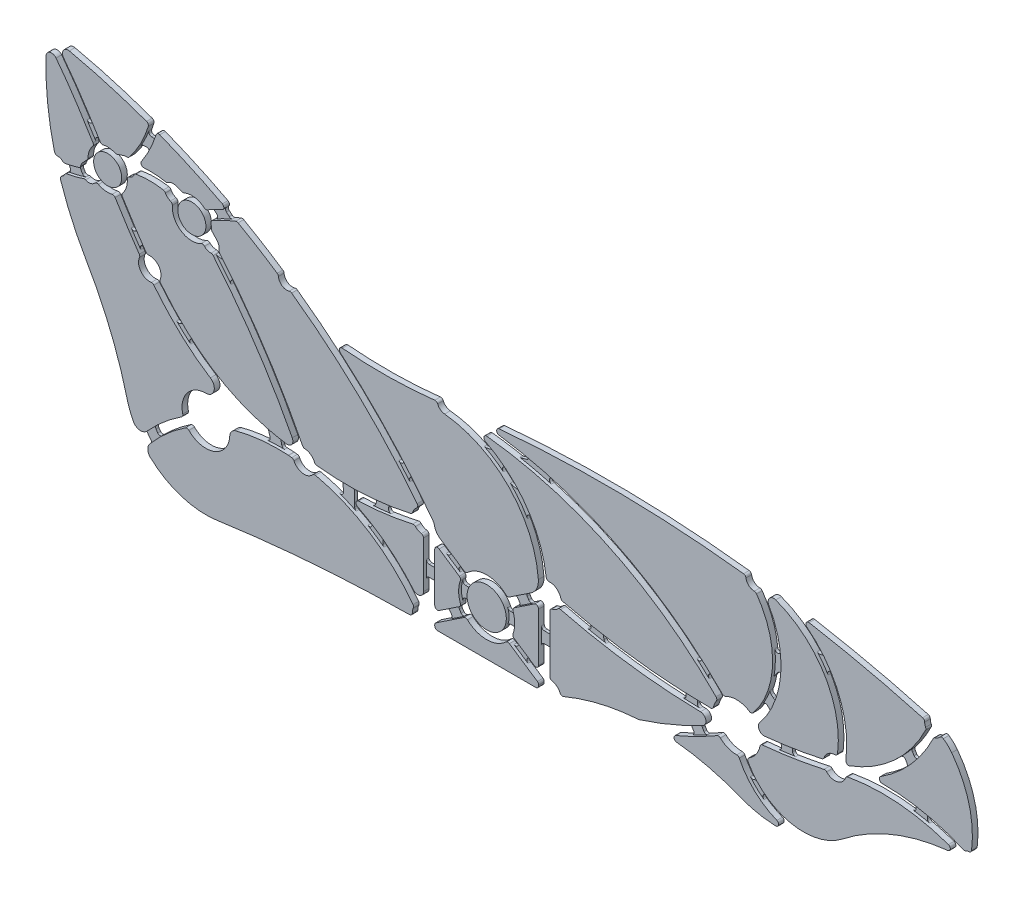
SolidWorks part; units mm, degrees
material "ｴﾎﾟｷｼ樹脂(充填剤なし)"
ref_plane "正面" through (0, 0, 0) normal (0, 0, 1) x (1, 0, 0)
ref_plane "平面" through (0, 0, 0) normal (0, 1, 0) x (1, 0, 0)
ref_plane "右側面" through (0, 0, 0) normal (1, 0, 0) x (0, 0, -1)
sketch "ｽｹｯﾁ1" plane through (0, 0, 0) normal (0, 0, 1) x (1, 0, 0)
  line L1 (22.5, 10.101) -> (22.5, -10.101)
  line L2 (22.5, 10.101) -> (22.5, -10.101)
  line L3 (-22.5, -6.4126) -> (-22.5, 10.101)
  line L4 (-22.5, -6.4126) -> (-22.5, 10.101)
  line L6 (8.081, 7.1901) -> (15.7442, 12.2989)
  line L7 (-16.9453, -9.4941) -> (-9.7451, -4.694)
  line L8 (-18.5, 8.662) -> (-18.5, -8.662)
  line L9 (-9.7451, 4.694) -> (-16.9453, 9.4941)
  line L10 (-16.9453, -9.4941) -> (-9.7451, -4.694)
  line L11 (-18.5, 8.662) -> (-18.5, -8.662)
  line L12 (-9.7451, 4.694) -> (-16.9453, 9.4941)
  line L13 (9.7451, -4.694) -> (16.9453, -9.4941)
  line L14 (16.9453, 9.4941) -> (9.7451, 4.694)
  line L15 (18.5, -8.662) -> (18.5, 8.662)
  line L16 (9.7451, -4.694) -> (16.9453, -9.4941)
  line L17 (16.9453, 9.4941) -> (9.7451, 4.694)
  line L18 (18.5, -8.662) -> (18.5, 8.662)
  line L19 (-16.4885, 12.7951) -> (-8.081, 7.1901)
  line L20 (8.081, 7.1901) -> (15.7442, 12.2989)
  line L21 (-16.4885, 12.7951) -> (-8.081, 7.1901)
  line L25 (-17.5, -16) -> (17.5, -16)
  line L26 (-18.5, -14.6713) -> (-18.5, -15)
  line L27 (-8.081, -7.1901) -> (-18.0547, -13.8392)
  line L28 (18.0547, -13.8392) -> (8.081, -7.1901)
  line L29 (18.5, -15) -> (18.5, -14.6713)
  line L30 (-17.5, -16) -> (17.5, -16)
  line L31 (-18.5, -14.6713) -> (-18.5, -15)
  line L32 (-8.081, -7.1901) -> (-18.0547, -13.8392)
  line L33 (18.0547, -13.8392) -> (8.081, -7.1901)
  line L34 (18.5, -15) -> (18.5, -14.6713)
  circle A11 centre (-105, 67.4812) radius 5
  circle A12 centre (-105, 67.4812) radius 5
  arc A15 (83.2113, 1.2758) -> (89.0603, -0.9998) centre (89, 7.5) ccw
  arc A16 (89.967, -1.5631) -> (89.0603, -0.9998) centre (89.0674, -1.9998) ccw
  arc A17 (89.967, -1.5631) -> (103.3566, -14.0607) centre (112.8701, 9.5532) ccw
  arc A18 (102.9573, -15.9879) -> (103.3566, -14.0607) centre (102.9829, -14.9883) ccw
  arc A19 (90.1176, -13.3365) -> (102.9573, -15.9879) centre (103.9017, 21) ccw
  arc A20 (90.1176, -13.3365) -> (67.6378, -7.8134) centre (59.3978, -89.8605) ccw
  arc A21 (67.3468, -5.898) -> (67.6378, -7.8134) centre (67.7378, -6.8184) ccw
  arc A22 (67.3468, -5.898) -> (82.0317, 1.4104) centre (13.9413, 119.818) ccw
  arc A23 (83.2113, 1.2758) -> (82.0317, 1.4104) centre (82.5302, 0.5435) ccw
  arc A24 (83.2113, 1.2758) -> (89.0603, -0.9998) centre (89, 7.5) ccw
  arc A25 (89.967, -1.5631) -> (89.0603, -0.9998) centre (89.0674, -1.9998) ccw
  arc A26 (89.967, -1.5631) -> (103.3566, -14.0607) centre (112.8701, 9.5532) ccw
  arc A27 (102.9573, -15.9879) -> (103.3566, -14.0607) centre (102.9829, -14.9883) ccw
  arc A28 (90.1176, -13.3365) -> (102.9573, -15.9879) centre (103.9017, 21) ccw
  arc A29 (90.1176, -13.3365) -> (67.6378, -7.8134) centre (59.3978, -89.8605) ccw
  arc A30 (67.3468, -5.898) -> (67.6378, -7.8134) centre (67.7378, -6.8184) ccw
  arc A31 (67.3468, -5.898) -> (82.0317, 1.4104) centre (13.9413, 119.818) ccw
  arc A32 (83.2113, 1.2758) -> (82.0317, 1.4104) centre (82.5302, 0.5435) ccw
  circle A33 centre (-135, 67.4812) radius 5
  arc A34 (129.2694, 15.7) -> (156.3313, 40.2464) centre (111.7928, 62.1584) ccw
  arc A35 (127.926, 16.7675) -> (129.2694, 15.7) centre (128.9173, 16.636) ccw
  arc A36 (127.926, 16.7675) -> (114.0595, 50.8962) centre (91.0356, 21.6602) ccw
  arc A37 (164.4555, 9.0239) -> (128.5785, 11.9436) centre (141.0399, -56.8173) ccw
  arc A38 (164.2263, 7.0873) -> (164.4555, 9.0239) centre (164.1205, 8.0817) ccw
  arc A39 (164.2263, 7.0873) -> (126.7209, -8.1253) centre (172, -65.9175) ccw
  arc A40 (93.0844, -1.0722) -> (126.7209, -8.1253) centre (112.8701, 9.5532) ccw
  arc A41 (93.4427, 0.2535) -> (93.0844, -1.0722) centre (93.9654, -0.5991) ccw
  arc A42 (93.4427, 0.2535) -> (97.334, 5.8282) centre (89, 7.5) ccw
  arc A43 (98.2209, 6.6271) -> (97.334, 5.8282) centre (98.3144, 5.6315) ccw
  arc A44 (98.2209, 6.6271) -> (120.135, 10.059) centre (81.3677, 185.9262) ccw
  arc A45 (121.0802, 9.766) -> (120.135, 10.059) centre (120.3503, 9.0824) ccw
  arc A46 (121.0802, 9.766) -> (120.135, 10.059) centre (120.3503, 9.0824) ccw
  arc A47 (121.0802, 9.766) -> (127.8055, 11.2677) centre (124, 12.5) ccw
  arc A48 (164.4555, 9.0239) -> (128.5785, 11.9436) centre (141.0399, -56.8173) ccw
  arc A49 (164.2263, 7.0873) -> (164.4555, 9.0239) centre (164.1205, 8.0817) ccw
  arc A50 (164.2263, 7.0873) -> (126.7209, -8.1253) centre (172, -65.9175) ccw
  arc A51 (93.0844, -1.0722) -> (126.7209, -8.1253) centre (112.8701, 9.5532) ccw
  arc A52 (93.4427, 0.2535) -> (93.0844, -1.0722) centre (93.9654, -0.5991) ccw
  arc A53 (93.4427, 0.2535) -> (97.334, 5.8282) centre (89, 7.5) ccw
  arc A54 (98.2209, 6.6271) -> (97.334, 5.8282) centre (98.3144, 5.6315) ccw
  arc A55 (98.2209, 6.6271) -> (120.135, 10.059) centre (81.3677, 185.9262) ccw
  arc A56 (121.0802, 9.766) -> (127.8055, 11.2677) centre (124, 12.5) ccw
  arc A57 (128.5785, 11.9436) -> (127.8055, 11.2677) centre (128.7568, 10.9597) ccw
  arc A58 (128.5785, 11.9436) -> (127.8055, 11.2677) centre (128.7568, 10.9597) ccw
  arc A59 (114.85, 52.6669) -> (114.0595, 50.8962) centre (114.6782, 51.6818) ccw
  arc A60 (155.2686, 43.5545) -> (114.85, 52.6669) centre (42.29, -363.3692) ccw
  arc A61 (156.0008, 42.5682) -> (155.2686, 43.5545) centre (155.001, 42.5909) ccw
  arc A62 (156.0008, 42.5682) -> (156.3255, 41.1409) centre (159, 42.5) ccw
  arc A63 (156.3313, 40.2464) -> (156.3255, 41.1409) centre (155.434, 40.6879) ccw
  arc A64 (129.2694, 15.7) -> (156.3313, 40.2464) centre (111.7928, 62.1584) ccw
  arc A65 (127.926, 16.7675) -> (129.2694, 15.7) centre (128.9173, 16.636) ccw
  arc A66 (127.926, 16.7675) -> (114.0595, 50.8962) centre (91.0356, 21.6602) ccw
  arc A67 (114.85, 52.6669) -> (114.0595, 50.8962) centre (114.6782, 51.6818) ccw
  arc A68 (155.2686, 43.5545) -> (114.85, 52.6669) centre (42.29, -363.3692) ccw
  arc A69 (156.0008, 42.5682) -> (155.2686, 43.5545) centre (155.001, 42.5909) ccw
  arc A70 (156.0008, 42.5682) -> (156.3255, 41.1409) centre (159, 42.5) ccw
  arc A71 (156.3313, 40.2464) -> (156.3255, 41.1409) centre (155.434, 40.6879) ccw
  arc A72 (97.2256, 12.9693) -> (98.9735, 9.7142) centre (98.7746, 11.7043) ccw
  arc A73 (97.2256, 12.9693) -> (100.5051, 50.879) centre (71.0713, 34.3286) ccw
  arc A74 (93.5868, 14.6562) -> (85.0963, 15.0506) centre (89, 7.5) ccw
  arc A75 (171.786, 10.4924) -> (170.6448, 10.1764) centre (172, 7.5) ccw
  arc A76 (169.7984, 10.1497) -> (170.6448, 10.1764) centre (170.193, 11.0686) ccw
  arc A77 (169.7984, 10.1497) -> (140.836, 16.0634) centre (141.0399, -56.8173) ccw
  arc A78 (140.2918, 17.9041) -> (140.836, 16.0634) centre (140.8332, 17.0634) ccw
  arc A79 (140.2918, 17.9041) -> (159.0925, 39.0635) centre (111.7928, 62.1584) ccw
  arc A80 (159.7433, 39.5935) -> (159.0925, 39.0635) centre (159.9911, 38.6247) ccw
  arc A81 (159.7433, 39.5935) -> (161.317, 40.5944) centre (159, 42.5) ccw
  arc A82 (162.6526, 40.7855) -> (161.317, 40.5944) centre (162.0894, 39.9592) ccw
  arc A83 (165.6353, 37.9447) -> (162.6526, 40.7855) centre (155.4945, 30.2837) ccw
  arc A84 (172.7066, 11.3632) -> (165.6353, 37.9447) centre (136.5587, 15.9784) ccw
  arc A85 (171.786, 10.4924) -> (172.7066, 11.3632) centre (171.7146, 11.4898) ccw
  arc A86 (171.786, 10.4924) -> (170.6448, 10.1764) centre (172, 7.5) ccw
  arc A87 (169.7984, 10.1497) -> (170.6448, 10.1764) centre (170.193, 11.0686) ccw
  arc A88 (169.7984, 10.1497) -> (140.836, 16.0634) centre (141.0399, -56.8173) ccw
  arc A89 (140.2918, 17.9041) -> (140.836, 16.0634) centre (140.8332, 17.0634) ccw
  arc A90 (140.2918, 17.9041) -> (159.0925, 39.0635) centre (111.7928, 62.1584) ccw
  arc A91 (159.7433, 39.5935) -> (159.0925, 39.0635) centre (159.9911, 38.6247) ccw
  arc A92 (159.7433, 39.5935) -> (161.317, 40.5944) centre (159, 42.5) ccw
  arc A93 (162.6526, 40.7855) -> (161.317, 40.5944) centre (162.0894, 39.9592) ccw
  arc A94 (165.6353, 37.9447) -> (162.6526, 40.7855) centre (155.4945, 30.2837) ccw
  arc A95 (172.7066, 11.3632) -> (165.6353, 37.9447) centre (136.5587, 15.9784) ccw
  arc A96 (171.786, 10.4924) -> (172.7066, 11.3632) centre (171.7146, 11.4898) ccw
  arc A97 (83.9236, 15.238) -> (85.0963, 15.0506) centre (84.637, 15.9389) ccw
  arc A98 (83.9236, 15.238) -> (4.4224, 55.2639) centre (-14.6672, -81.6202) ccw
  arc A99 (4.471, 57.2503) -> (4.4224, 55.2639) centre (4.5606, 56.2543) ccw
  arc A100 (91.4838, 56.0721) -> (4.471, 57.2503) centre (42.29, -363.3692) ccw
  arc A101 (92.3587, 55.2099) -> (91.4838, 56.0721) centre (91.3673, 55.0789) ccw
  arc A102 (92.3587, 55.2099) -> (95.319, 52.6028) centre (95.3328, 55.6027) ccw
  arc A103 (96.1287, 52.1831) -> (95.319, 52.6028) centre (95.3143, 51.6028) ccw
  arc A104 (94.9009, 14.8656) -> (96.1287, 52.1831) centre (71.0713, 34.3286) ccw
  arc A105 (93.5868, 14.6562) -> (94.9009, 14.8656) centre (94.1264, 15.4981) ccw
  arc A106 (93.5868, 14.6562) -> (85.0963, 15.0506) centre (89, 7.5) ccw
  arc A107 (83.9236, 15.238) -> (85.0963, 15.0506) centre (84.637, 15.9389) ccw
  arc A108 (83.9236, 15.238) -> (4.4224, 55.2639) centre (-14.6672, -81.6202) ccw
  arc A109 (4.471, 57.2503) -> (4.4224, 55.2639) centre (4.5606, 56.2543) ccw
  arc A110 (91.4838, 56.0721) -> (4.471, 57.2503) centre (42.29, -363.3692) ccw
  arc A111 (92.3587, 55.2099) -> (91.4838, 56.0721) centre (91.3673, 55.0789) ccw
  arc A112 (92.3587, 55.2099) -> (95.319, 52.6028) centre (95.3328, 55.6027) ccw
  arc A113 (96.1287, 52.1831) -> (95.319, 52.6028) centre (95.3143, 51.6028) ccw
  arc A114 (94.9009, 14.8656) -> (96.1287, 52.1831) centre (71.0713, 34.3286) ccw
  arc A115 (93.5868, 14.6562) -> (94.9009, 14.8656) centre (94.1264, 15.4981) ccw
  arc A116 (81.6673, 13.2539) -> (0.0815, 52.7818) centre (-14.6672, -81.6202) ccw
  arc A117 (81.8017, 12.0204) -> (81.6673, 13.2539) centre (80.9548, 12.5522) ccw
  arc A118 (81.8017, 12.0204) -> (80.7533, 9.5597) centre (89, 7.5) ccw
  arc A119 (79.7833, 8.8021) -> (80.7533, 9.5597) centre (79.7831, 9.8021) ccw
  arc A120 (27.0791, 15.346) -> (79.7833, 8.8021) centre (79.7405, 223.9658) ccw
  arc A121 (26.3591, 16.0525) -> (27.0791, 15.346) centre (27.3238, 16.3156) ccw
  arc A122 (26.3591, 16.0525) -> (22.2579, 18.9927) centre (22.5, 15) ccw
  arc A123 (21.2047, 19.87) -> (22.2579, 18.9927) centre (22.1973, 19.9908) ccw
  arc A124 (21.2047, 19.87) -> (-0.4821, 50.897) centre (-18.8012, 15) ccw
  arc A125 (0.0815, 52.7818) -> (-0.4821, 50.897) centre (-0.0275, 51.7877) ccw
  arc A126 (81.6673, 13.2539) -> (0.0815, 52.7818) centre (-14.6672, -81.6202) ccw
  arc A127 (81.8017, 12.0204) -> (81.6673, 13.2539) centre (80.9548, 12.5522) ccw
  arc A128 (81.8017, 12.0204) -> (80.7533, 9.5597) centre (89, 7.5) ccw
  arc A129 (79.7833, 8.8021) -> (80.7533, 9.5597) centre (79.7831, 9.8021) ccw
  arc A130 (27.0791, 15.346) -> (79.7833, 8.8021) centre (79.7405, 223.9658) ccw
  arc A131 (26.3591, 16.0525) -> (27.0791, 15.346) centre (27.3238, 16.3156) ccw
  arc A132 (26.3591, 16.0525) -> (22.2579, 18.9927) centre (22.5, 15) ccw
  arc A133 (21.2047, 19.87) -> (22.2579, 18.9927) centre (22.1973, 19.9908) ccw
  arc A134 (21.2047, 19.87) -> (-0.4821, 50.897) centre (-18.8012, 15) ccw
  arc A135 (0.0815, 52.7818) -> (-0.4821, 50.897) centre (-0.0275, 51.7877) ccw
  arc A136 (102.9446, 53.7342) -> (100.5051, 50.879) centre (102.2484, 51.8592) ccw
  arc A137 (23.3, 11.0808) -> (25.3408, 12.184) centre (22.5, 15) ccw
  arc A138 (26.296, 12.4496) -> (25.3408, 12.184) centre (26.0511, 11.4801) ccw
  arc A139 (26.296, 12.4496) -> (76.128, 5.832) centre (79.7405, 223.9658) ccw
  arc A140 (77.0395, 2.0694) -> (76.128, 5.832) centre (76.0949, 3.8322) ccw
  arc A141 (54.3014, -7.5287) -> (77.0395, 2.0694) centre (13.9413, 119.818) ccw
  arc A142 (54.0639, -7.5734) -> (54.3014, -7.5287) centre (53.9993, -6.5755) ccw
  arc A143 (54.0639, -7.5734) -> (27.4366, -13.8466) centre (59.3978, -89.8605) ccw
  arc A144 (26.1392, -13.3399) -> (27.4366, -13.8466) centre (27.049, -12.9248) ccw
  arc A145 (26.1392, -13.3399) -> (23.3, -11.0808) centre (22.5, -15) ccw
  arc A146 (22.5, -10.101) -> (23.3, -11.0808) centre (23.5, -10.101) ccw
  arc A147 (23.3, 11.0808) -> (22.5, 10.101) centre (23.5, 10.101) ccw
  arc A148 (23.3, 11.0808) -> (25.3408, 12.184) centre (22.5, 15) ccw
  arc A149 (26.296, 12.4496) -> (25.3408, 12.184) centre (26.0511, 11.4801) ccw
  arc A150 (26.296, 12.4496) -> (76.128, 5.832) centre (79.7405, 223.9658) ccw
  arc A151 (77.0395, 2.0694) -> (76.128, 5.832) centre (76.0949, 3.8322) ccw
  arc A152 (54.3014, -7.5287) -> (77.0395, 2.0694) centre (13.9413, 119.818) ccw
  arc A153 (54.0639, -7.5734) -> (54.3014, -7.5287) centre (53.9993, -6.5755) ccw
  arc A154 (54.0639, -7.5734) -> (27.4366, -13.8466) centre (59.3978, -89.8605) ccw
  arc A155 (26.1392, -13.3399) -> (27.4366, -13.8466) centre (27.049, -12.9248) ccw
  arc A156 (26.1392, -13.3399) -> (23.3, -11.0808) centre (22.5, -15) ccw
  arc A157 (22.5, -10.101) -> (23.3, -11.0808) centre (23.5, -10.101) ccw
  arc A158 (23.3, 11.0808) -> (22.5, 10.101) centre (23.5, 10.101) ccw
  arc A159 (124.9796, 17.3747) -> (102.9446, 53.7342) centre (91.0356, 21.6602) ccw
  arc A160 (123.99, 16.5) -> (124.9796, 17.3747) centre (123.9875, 17.5) ccw
  arc A161 (123.99, 16.5) -> (124.9796, 17.3747) centre (123.9875, 17.5) ccw
  arc A162 (123.99, 16.5) -> (120.1725, 13.6619) centre (124, 12.5) ccw
  arc A163 (98.9735, 9.7142) -> (119.4305, 12.9757) centre (81.3677, 185.9262) ccw
  arc A164 (97.2256, 12.9693) -> (98.9735, 9.7142) centre (98.7746, 11.7043) ccw
  arc A165 (97.2256, 12.9693) -> (100.5051, 50.879) centre (71.0713, 34.3286) ccw
  arc A166 (102.9446, 53.7342) -> (100.5051, 50.879) centre (102.2484, 51.8592) ccw
  arc A167 (124.9796, 17.3747) -> (102.9446, 53.7342) centre (91.0356, 21.6602) ccw
  arc A168 (123.99, 16.5) -> (120.1725, 13.6619) centre (124, 12.5) ccw
  arc A169 (119.4305, 12.9757) -> (120.1725, 13.6619) centre (119.2156, 13.9524) ccw
  arc A170 (119.4305, 12.9757) -> (120.1725, 13.6619) centre (119.2156, 13.9524) ccw
  arc A171 (98.9735, 9.7142) -> (119.4305, 12.9757) centre (81.3677, 185.9262) ccw
  circle A172 centre (-135, 67.4812) radius 5
  arc A179 (-9.3634, 3.5108) -> (-9.3634, -3.5108) centre (0, 0) ccw
  arc A180 (-9.7451, -4.694) -> (-9.3634, -3.5108) centre (-10.2998, -3.8619) ccw
  arc A181 (-25.3716, 12.2154) -> (-23.3, 11.0808) centre (-22.5, 15) ccw
  arc A182 (-22.5, 10.101) -> (-23.3, 11.0808) centre (-23.5, 10.101) ccw
  arc A183 (-26.0294, -7.7013) -> (-22.5, -6.4126) centre (-24.5, -6.4126) ccw
  arc A184 (-150.1749, 61.8391) -> (-145.3174, 63.0063) centre (-156.5, 98.8544) ccw
  arc A185 (-150.9937, 62.0651) -> (-150.1749, 61.8391) centre (-150.3434, 62.8248) ccw
  arc A186 (-150.9937, 62.0651) -> (-152.9688, 62.786) centre (-152.9445, 59.7861) ccw
  arc A187 (-153.9477, 63.5462) -> (-152.9688, 62.786) centre (-152.9768, 63.786) ccw
  arc A188 (-156.9598, 91.5374) -> (-153.9477, 63.5462) centre (-52.35, 88.6367) ccw
  arc A189 (-153.381, 92.7088) -> (-156.9598, 91.5374) centre (-154.9606, 91.482) ccw
  arc A190 (-140.3222, 72.0281) -> (-140.2301, 73.2004) centre (-141.0826, 72.6776) ccw
  arc A191 (-140.3222, 72.0281) -> (-141.9993, 67.5789) centre (-135, 67.4812) ccw
  arc A192 (-142.2946, 66.8832) -> (-141.9993, 67.5789) centre (-142.9992, 67.5928) ccw
  arc A193 (-89.4045, 74.3517) -> (-97.7506, 70.3671) centre (-65, 12.5) ccw
  arc A194 (-88.5457, 74.2922) -> (-89.4045, 74.3517) centre (-89.0375, 73.4215) ccw
  arc A195 (-74.6081, 65.7118) -> (-88.5457, 74.2922) centre (-195.2577, -114.6564) ccw
  arc A196 (-74.1672, 64.9589) -> (-74.6081, 65.7118) centre (-75.1641, 64.8806) ccw
  arc A197 (-74.1672, 64.9589) -> (-74.6081, 65.7118) centre (-75.1641, 64.8806) ccw
  arc A198 (-74.1672, 64.9589) -> (-70.3341, 62.3144) centre (-71.1764, 65.1938) ccw
  arc A199 (-74.1672, 64.9589) -> (-70.3341, 62.3144) centre (-71.1764, 65.1938) ccw
  arc A200 (-24.9379, 18.1712) -> (-24.7617, 19.5826) centre (-25.5474, 18.964) ccw
  arc A201 (-24.9379, 18.1712) -> (-26.3471, 16.0955) centre (-22.5, 15) ccw
  arc A202 (-27.086, 15.3946) -> (-26.3471, 16.0955) centre (-27.3088, 16.3694) ccw
  arc A203 (-60.4919, 13.4295) -> (-27.086, 15.3946) centre (-49.6549, 114.1334) ccw
  arc A204 (-69.4737, 62.1695) -> (-70.3341, 62.3144) centre (-70.0534, 61.3546) ccw
  arc A205 (-69.4737, 62.1695) -> (-70.3341, 62.3144) centre (-70.0534, 61.3546) ccw
  arc A206 (-24.7617, 19.5826) -> (-69.4737, 62.1695) centre (-195.2577, -114.6564) ccw
  arc A207 (-65.5834, 17.0366) -> (-95.1344, 61.7139) centre (-276.8279, -90.5756) ccw
  arc A208 (-95.3497, 62.5466) -> (-95.1344, 61.7139) centre (-94.368, 62.3562) ccw
  arc A209 (-95.3497, 62.5466) -> (-96.0213, 65.0748) centre (-98.2949, 63.1176) ccw
  arc A210 (-96.0213, 65.0748) -> (-97.7054, 66.8832) centre (-120, 44.4324) ccw
  arc A211 (-98.0007, 67.5789) -> (-97.7054, 66.8832) centre (-97.0008, 67.5928) ccw
  arc A212 (-98.0007, 67.5789) -> (-98.2258, 69.2449) centre (-105, 67.4812) ccw
  arc A213 (-97.7506, 70.3671) -> (-98.2258, 69.2449) centre (-97.2581, 69.4969) ccw
  arc A214 (-89.4045, 74.3517) -> (-97.7506, 70.3671) centre (-65, 12.5) ccw
  arc A215 (-88.5457, 74.2922) -> (-89.4045, 74.3517) centre (-89.0375, 73.4215) ccw
  arc A216 (-74.6081, 65.7118) -> (-88.5457, 74.2922) centre (-195.2577, -114.6564) ccw
  arc A217 (-24.7617, 19.5826) -> (-69.4737, 62.1695) centre (-195.2577, -114.6564) ccw
  arc A218 (-61.3079, 14.039) -> (-60.4919, 13.4295) centre (-60.3849, 14.4238) ccw
  arc A219 (-61.3079, 14.039) -> (-60.4919, 13.4295) centre (-60.3849, 14.4238) ccw
  arc A220 (-61.3079, 14.039) -> (-64.7539, 16.4924) centre (-65, 12.5) ccw
  arc A221 (-24.9379, 18.1712) -> (-24.7617, 19.5826) centre (-25.5474, 18.964) ccw
  arc A222 (-24.9379, 18.1712) -> (-26.3471, 16.0955) centre (-22.5, 15) ccw
  arc A223 (-27.086, 15.3946) -> (-26.3471, 16.0955) centre (-27.3088, 16.3694) ccw
  arc A224 (-60.4919, 13.4295) -> (-27.086, 15.3946) centre (-49.6549, 114.1334) ccw
  arc A225 (-61.3079, 14.039) -> (-64.7539, 16.4924) centre (-65, 12.5) ccw
  arc A226 (-65.5834, 17.0366) -> (-64.7539, 16.4924) centre (-64.6924, 17.4905) ccw
  arc A227 (-65.5834, 17.0366) -> (-64.7539, 16.4924) centre (-64.6924, 17.4905) ccw
  arc A228 (-65.5834, 17.0366) -> (-95.1344, 61.7139) centre (-276.8279, -90.5756) ccw
  arc A229 (-95.3497, 62.5466) -> (-95.1344, 61.7139) centre (-94.368, 62.3562) ccw
  arc A230 (-95.3497, 62.5466) -> (-96.0213, 65.0748) centre (-98.2949, 63.1176) ccw
  arc A231 (-96.0213, 65.0748) -> (-97.7054, 66.8832) centre (-120, 44.4324) ccw
  arc A232 (-98.0007, 67.5789) -> (-97.7054, 66.8832) centre (-97.0008, 67.5928) ccw
  arc A233 (-98.0007, 67.5789) -> (-98.2258, 69.2449) centre (-105, 67.4812) ccw
  arc A234 (-97.7506, 70.3671) -> (-98.2258, 69.2449) centre (-97.2581, 69.4969) ccw
  arc A235 (-142.2946, 66.8832) -> (-143.9787, 65.0748) centre (-120, 44.4324) ccw
  arc A236 (-143.9787, 65.0748) -> (-144.6377, 63.7501) centre (-141.7051, 63.1176) ccw
  arc A237 (-145.3174, 63.0063) -> (-144.6377, 63.7501) centre (-145.6152, 63.9609) ccw
  arc A238 (-150.1749, 61.8391) -> (-145.3174, 63.0063) centre (-156.5, 98.8544) ccw
  arc A239 (-150.9937, 62.0651) -> (-150.1749, 61.8391) centre (-150.3434, 62.8248) ccw
  arc A240 (-150.9937, 62.0651) -> (-152.9688, 62.786) centre (-152.9445, 59.7861) ccw
  arc A241 (-153.9477, 63.5462) -> (-152.9688, 62.786) centre (-152.9768, 63.786) ccw
  arc A242 (-156.9598, 91.5374) -> (-153.9477, 63.5462) centre (-52.35, 88.6367) ccw
  arc A243 (-153.381, 92.7088) -> (-156.9598, 91.5374) centre (-154.9606, 91.482) ccw
  arc A244 (-140.3222, 72.0281) -> (-140.2301, 73.2004) centre (-141.0826, 72.6776) ccw
  arc A245 (-140.3222, 72.0281) -> (-141.9993, 67.5789) centre (-135, 67.4812) ccw
  arc A246 (-142.2946, 66.8832) -> (-141.9993, 67.5789) centre (-142.9992, 67.5928) ccw
  arc A247 (-142.2946, 66.8832) -> (-143.9787, 65.0748) centre (-120, 44.4324) ccw
  arc A248 (-143.9787, 65.0748) -> (-144.6377, 63.7501) centre (-141.7051, 63.1176) ccw
  arc A249 (-145.3174, 63.0063) -> (-144.6377, 63.7501) centre (-145.6152, 63.9609) ccw
  arc A250 (-26.0294, -7.7013) -> (-46.0024, 8.0337) centre (-74.1755, -48.2713) ccw
  arc A251 (-45.5939, 9.9272) -> (-46.0024, 8.0337) centre (-45.555, 8.9279) ccw
  arc A252 (-45.5939, 9.9272) -> (-26.3133, 12.4939) centre (-49.6549, 114.1334) ccw
  arc A253 (-122.9601, 76.0613) -> (-117.7547, 86.8856) centre (-156.5, 98.8544) ccw
  arc A254 (-116.4361, 87.5221) -> (-117.7547, 86.8856) centre (-116.7993, 86.5904) ccw
  arc A255 (-94.1545, 77.3518) -> (-116.4361, 87.5221) centre (-195.2577, -114.6564) ccw
  arc A256 (-94.2003, 75.5596) -> (-94.1545, 77.3518) centre (-94.6204, 76.467) ccw
  arc A257 (-94.2003, 75.5596) -> (-99.4771, 72.8365) centre (-65, 12.5) ccw
  arc A258 (-100.6016, 72.9268) -> (-99.4771, 72.8365) centre (-99.9733, 73.7047) ccw
  arc A259 (-100.6016, 72.9268) -> (-107.7452, 73.9205) centre (-105, 67.4812) ccw
  arc A260 (-108.5008, 73.9088) -> (-107.7452, 73.9205) centre (-108.1373, 74.8404) ccw
  arc A261 (-108.5008, 73.9088) -> (-110.8362, 74.7163) centre (-120, 44.4324) ccw
  arc A262 (-110.8362, 74.7163) -> (-113.5331, 74.2236) centre (-111.7051, 71.8449) ccw
  arc A263 (-114.3306, 74.0344) -> (-113.5331, 74.2236) centre (-114.1425, 75.0165) ccw
  arc A264 (-114.3306, 74.0344) -> (-122.0645, 74.5016) centre (-120, 44.4324) ccw
  arc A265 (-122.9601, 76.0613) -> (-122.0645, 74.5016) centre (-122.133, 75.4992) ccw
  arc A266 (-122.9601, 76.0613) -> (-117.7547, 86.8856) centre (-156.5, 98.8544) ccw
  arc A267 (-116.4361, 87.5221) -> (-117.7547, 86.8856) centre (-116.7993, 86.5904) ccw
  arc A268 (-94.1545, 77.3518) -> (-116.4361, 87.5221) centre (-195.2577, -114.6564) ccw
  arc A269 (-94.2003, 75.5596) -> (-94.1545, 77.3518) centre (-94.6204, 76.467) ccw
  arc A270 (-94.2003, 75.5596) -> (-99.4771, 72.8365) centre (-65, 12.5) ccw
  arc A271 (-100.6016, 72.9268) -> (-99.4771, 72.8365) centre (-99.9733, 73.7047) ccw
  arc A272 (-100.6016, 72.9268) -> (-107.7452, 73.9205) centre (-105, 67.4812) ccw
  arc A273 (-108.5008, 73.9088) -> (-107.7452, 73.9205) centre (-108.1373, 74.8404) ccw
  arc A274 (-108.5008, 73.9088) -> (-110.8362, 74.7163) centre (-120, 44.4324) ccw
  arc A275 (-110.8362, 74.7163) -> (-113.5331, 74.2236) centre (-111.7051, 71.8449) ccw
  arc A276 (-114.3306, 74.0344) -> (-113.5331, 74.2236) centre (-114.1425, 75.0165) ccw
  arc A277 (-114.3306, 74.0344) -> (-122.0645, 74.5016) centre (-120, 44.4324) ccw
  arc A278 (-122.9601, 76.0613) -> (-122.0645, 74.5016) centre (-122.133, 75.4992) ccw
  arc A279 (-25.3716, 12.2154) -> (-26.3133, 12.4939) centre (-26.0895, 11.5192) ccw
  arc A280 (-25.3716, 12.2154) -> (-23.3, 11.0808) centre (-22.5, 15) ccw
  arc A281 (-22.5, 10.101) -> (-23.3, 11.0808) centre (-23.5, 10.101) ccw
  arc A282 (-26.0294, -7.7013) -> (-22.5, -6.4126) centre (-24.5, -6.4126) ccw
  arc A283 (-106.0705, 1.5503) -> (-91.5134, 7.0221) centre (-100, 7.5) ccw
  arc A284 (-89.2736, 9.7568) -> (-91.5134, 7.0221) centre (-88.5182, 6.8535) ccw
  arc A285 (-70.6217, 11.5834) -> (-89.2736, 9.7568) centre (-74.1755, -48.2713) ccw
  arc A286 (-70.544, 11.5757) -> (-70.6217, 11.5834) centre (-70.681, 10.5851) ccw
  arc A287 (-70.544, 11.5757) -> (-69.4318, 11.4299) centre (-59.6286, 90.5152) ccw
  arc A288 (-68.6438, 10.85) -> (-69.4318, 11.4299) centre (-69.5548, 10.4375) ccw
  arc A289 (-68.6438, 10.85) -> (-69.4318, 11.4299) centre (-69.5548, 10.4375) ccw
  arc A290 (-68.6438, 10.85) -> (-61.9641, 9.8955) centre (-65, 12.5) ccw
  arc A291 (-26.225, -12.2719) -> (-60.9851, 10.2199) centre (-74.1755, -48.2713) ccw
  arc A292 (-26.1198, -13.2978) -> (-26.225, -12.2719) centre (-27.0247, -12.8723) ccw
  arc A293 (-26.1198, -13.2978) -> (-26.5, -15.0192) centre (-22.5, -15) ccw
  arc A294 (-27.4903, -16.024) -> (-26.5, -15.0192) centre (-27.4999, -15.024) ccw
  arc A295 (-27.4903, -16.024) -> (-95.9045, -21.2094) centre (-22.5, -535.7727) ccw
  arc A296 (-119.7512, -13.7341) -> (-95.9045, -21.2094) centre (-100, 7.5) ccw
  arc A297 (-120.0008, -9.6028) -> (-119.7512, -13.7341) centre (-117.708, -11.5375) ccw
  arc A298 (-107.3377, 1.6835) -> (-120.0008, -9.6028) centre (-74.1755, -48.2713) ccw
  arc A299 (-106.0705, 1.5503) -> (-107.3377, 1.6835) centre (-106.7847, 0.8503) ccw
  arc A300 (-106.0705, 1.5503) -> (-91.5134, 7.0221) centre (-100, 7.5) ccw
  arc A301 (-89.2736, 9.7568) -> (-91.5134, 7.0221) centre (-88.5182, 6.8535) ccw
  arc A302 (-70.6217, 11.5834) -> (-89.2736, 9.7568) centre (-74.1755, -48.2713) ccw
  arc A303 (-70.544, 11.5757) -> (-70.6217, 11.5834) centre (-70.681, 10.5851) ccw
  arc A304 (-70.544, 11.5757) -> (-69.4318, 11.4299) centre (-59.6286, 90.5152) ccw
  arc A305 (-68.6438, 10.85) -> (-61.9641, 9.8955) centre (-65, 12.5) ccw
  arc A306 (-60.9851, 10.2199) -> (-61.9641, 9.8955) centre (-61.2051, 9.2444) ccw
  arc A307 (-60.9851, 10.2199) -> (-61.9641, 9.8955) centre (-61.2051, 9.2444) ccw
  arc A308 (-26.225, -12.2719) -> (-60.9851, 10.2199) centre (-74.1755, -48.2713) ccw
  arc A309 (-26.1198, -13.2978) -> (-26.225, -12.2719) centre (-27.0247, -12.8723) ccw
  arc A310 (-26.1198, -13.2978) -> (-26.5, -15.0192) centre (-22.5, -15) ccw
  arc A311 (-27.4903, -16.024) -> (-26.5, -15.0192) centre (-27.4999, -15.024) ccw
  arc A312 (-27.4903, -16.024) -> (-95.9045, -21.2094) centre (-22.5, -535.7727) ccw
  arc A313 (-119.7512, -13.7341) -> (-95.9045, -21.2094) centre (-100, 7.5) ccw
  arc A314 (-120.0008, -9.6028) -> (-119.7512, -13.7341) centre (-117.708, -11.5375) ccw
  arc A315 (-107.3377, 1.6835) -> (-120.0008, -9.6028) centre (-74.1755, -48.2713) ccw
  arc A316 (-106.0705, 1.5503) -> (-107.3377, 1.6835) centre (-106.7847, 0.8503) ccw
  arc A317 (-26.0294, -7.7013) -> (-46.0024, 8.0337) centre (-74.1755, -48.2713) ccw
  arc A318 (-45.5939, 9.9272) -> (-46.0024, 8.0337) centre (-45.555, 8.9279) ccw
  arc A319 (-45.5939, 9.9272) -> (-26.3133, 12.4939) centre (-49.6549, 114.1334) ccw
  arc A320 (-25.3716, 12.2154) -> (-26.3133, 12.4939) centre (-26.0895, 11.5192) ccw
  arc A321 (-18.5, -8.662) -> (-16.9453, -9.4941) centre (-17.5, -8.662) ccw
  arc A322 (-16.9453, 9.4941) -> (-18.5, 8.662) centre (-17.5, 8.662) ccw
  arc A323 (-9.3634, 3.5108) -> (-9.7451, 4.694) centre (-10.2998, 3.8619) ccw
  arc A324 (-148.6552, 97.2804) -> (-150.6693, 94.1069) centre (-149.0847, 95.3271) ccw
  arc A325 (-121.1468, 89.296) -> (-148.6552, 97.2804) centre (-195.2577, -114.6564) ccw
  arc A326 (-120.5304, 88.0689) -> (-121.1468, 89.296) centre (-121.4883, 88.3561) ccw
  arc A327 (-127.3262, 75.2106) -> (-120.5304, 88.0689) centre (-156.5, 98.8544) ccw
  arc A328 (-128.151, 74.8414) -> (-127.3262, 75.2106) centre (-128.1031, 75.8403) ccw
  arc A329 (-128.151, 74.8414) -> (-129.1638, 74.7163) centre (-128.2949, 71.8449) ccw
  arc A330 (-129.1638, 74.7163) -> (-131.4992, 73.9088) centre (-120, 44.4324) ccw
  arc A331 (-132.2548, 73.9205) -> (-131.4992, 73.9088) centre (-131.8627, 74.8404) ccw
  arc A332 (-100.5079, 61.0921) -> (-98.2079, 60.1189) centre (-98.2949, 63.1176) ccw
  arc A333 (-97.4124, 59.7615) -> (-98.2079, 60.1189) centre (-98.1789, 59.1193) ccw
  arc A334 (-69.2613, 17.6245) -> (-97.4124, 59.7615) centre (-276.8279, -90.5756) ccw
  arc A335 (-71.3387, 14.7232) -> (-69.2613, 17.6245) centre (-71.0348, 16.7) ccw
  arc A336 (-116.298, 42.9173) -> (-116.1523, 41.9125) centre (-115.3725, 42.5386) ccw
  arc A337 (-116.298, 42.9173) -> (-120.4138, 48.4109) centre (-120, 44.4324) ccw
  arc A338 (-121.3351, 48.83) -> (-120.4138, 48.4109) centre (-120.5173, 49.4055) ccw
  arc A339 (-129.673, 62.9399) -> (-129.7634, 61.7667) centre (-128.912, 62.2912) ccw
  arc A340 (-129.673, 62.9399) -> (-128.0179, 67.9818) centre (-135, 67.4812) ccw
  arc A341 (-127.3391, 69.0012) -> (-128.0179, 67.9818) centre (-127.0205, 68.0533) ccw
  arc A342 (-127.3391, 69.0012) -> (-125.5769, 70.575) centre (-128.2949, 71.8449) ccw
  arc A343 (-124.8496, 71.1356) -> (-125.5769, 70.575) centre (-124.6709, 70.1517) ccw
  arc A344 (-115.1504, 71.1356) -> (-124.8496, 71.1356) centre (-120, 44.4324) ccw
  arc A345 (-114.4231, 70.575) -> (-115.1504, 71.1356) centre (-115.3291, 70.1517) ccw
  arc A346 (-114.4231, 70.575) -> (-112.6609, 69.0012) centre (-111.7051, 71.8449) ccw
  arc A347 (-111.9821, 67.9818) -> (-112.6609, 69.0012) centre (-112.9795, 68.0533) ccw
  arc A348 (-111.9821, 67.9818) -> (-101.7149, 61.3) centre (-105, 67.4812) ccw
  arc A349 (-100.5079, 61.0921) -> (-101.7149, 61.3) centre (-101.2456, 60.4169) ccw
  arc A350 (-100.5079, 61.0921) -> (-98.2079, 60.1189) centre (-98.2949, 63.1176) ccw
  arc A351 (-97.4124, 59.7615) -> (-98.2079, 60.1189) centre (-98.1789, 59.1193) ccw
  arc A352 (-69.2613, 17.6245) -> (-97.4124, 59.7615) centre (-276.8279, -90.5756) ccw
  arc A353 (-71.3387, 14.7232) -> (-69.2613, 17.6245) centre (-71.0348, 16.7) ccw
  arc A354 (-116.298, 42.9173) -> (-116.1523, 41.9125) centre (-115.3725, 42.5386) ccw
  arc A355 (-116.298, 42.9173) -> (-120.4138, 48.4109) centre (-120, 44.4324) ccw
  arc A356 (-121.3351, 48.83) -> (-120.4138, 48.4109) centre (-120.5173, 49.4055) ccw
  arc A357 (-129.673, 62.9399) -> (-129.7634, 61.7667) centre (-128.912, 62.2912) ccw
  arc A358 (-129.673, 62.9399) -> (-128.0179, 67.9818) centre (-135, 67.4812) ccw
  arc A359 (-127.3391, 69.0012) -> (-128.0179, 67.9818) centre (-127.0205, 68.0533) ccw
  arc A360 (-127.3391, 69.0012) -> (-125.5769, 70.575) centre (-128.2949, 71.8449) ccw
  arc A361 (-124.8496, 71.1356) -> (-125.5769, 70.575) centre (-124.6709, 70.1517) ccw
  arc A362 (-115.1504, 71.1356) -> (-124.8496, 71.1356) centre (-120, 44.4324) ccw
  arc A363 (-114.4231, 70.575) -> (-115.1504, 71.1356) centre (-115.3291, 70.1517) ccw
  arc A364 (-114.4231, 70.575) -> (-112.6609, 69.0012) centre (-111.7051, 71.8449) ccw
  arc A365 (-111.9821, 67.9818) -> (-112.6609, 69.0012) centre (-112.9795, 68.0533) ccw
  arc A366 (-111.9821, 67.9818) -> (-101.7149, 61.3) centre (-105, 67.4812) ccw
  arc A367 (-100.5079, 61.0921) -> (-101.7149, 61.3) centre (-101.2456, 60.4169) ccw
  arc A368 (-132.2548, 73.9205) -> (-136.5835, 74.2998) centre (-135, 67.4812) ccw
  arc A369 (-137.6622, 74.7511) -> (-136.5835, 74.2998) centre (-136.8097, 75.2738) ccw
  arc A370 (-148.6552, 97.2804) -> (-150.6693, 94.1069) centre (-149.0847, 95.3271) ccw
  arc A371 (-121.1468, 89.296) -> (-148.6552, 97.2804) centre (-195.2577, -114.6564) ccw
  arc A372 (-120.5304, 88.0689) -> (-121.1468, 89.296) centre (-121.4883, 88.3561) ccw
  arc A373 (-127.3262, 75.2106) -> (-120.5304, 88.0689) centre (-156.5, 98.8544) ccw
  arc A374 (-128.151, 74.8414) -> (-127.3262, 75.2106) centre (-128.1031, 75.8403) ccw
  arc A375 (-128.151, 74.8414) -> (-129.1638, 74.7163) centre (-128.2949, 71.8449) ccw
  arc A376 (-129.1638, 74.7163) -> (-131.4992, 73.9088) centre (-120, 44.4324) ccw
  arc A377 (-132.2548, 73.9205) -> (-131.4992, 73.9088) centre (-131.8627, 74.8404) ccw
  arc A378 (-132.2548, 73.9205) -> (-136.5835, 74.2998) centre (-135, 67.4812) ccw
  arc A379 (-137.6622, 74.7511) -> (-136.5835, 74.2998) centre (-136.8097, 75.2738) ccw
  arc A380 (-9.3634, 3.5108) -> (-9.3634, -3.5108) centre (0, 0) ccw
  arc A381 (-9.7451, -4.694) -> (-9.3634, -3.5108) centre (-10.2998, -3.8619) ccw
  arc A382 (-18.5, -8.662) -> (-16.9453, -9.4941) centre (-17.5, -8.662) ccw
  arc A383 (-16.9453, 9.4941) -> (-18.5, 8.662) centre (-17.5, 8.662) ccw
  arc A384 (-9.3634, 3.5108) -> (-9.7451, 4.694) centre (-10.2998, 3.8619) ccw
  arc A385 (9.3634, -3.5108) -> (9.7451, -4.694) centre (10.2998, -3.8619) ccw
  arc A386 (9.3634, -3.5108) -> (9.3634, 3.5108) centre (0, 0) ccw
  arc A387 (9.7451, 4.694) -> (9.3634, 3.5108) centre (10.2998, 3.8619) ccw
  arc A388 (18.5, 8.662) -> (16.9453, 9.4941) centre (17.5, 8.662) ccw
  arc A389 (16.9453, -9.4941) -> (18.5, -8.662) centre (17.5, -8.662) ccw
  arc A390 (9.3634, -3.5108) -> (9.7451, -4.694) centre (10.2998, -3.8619) ccw
  arc A391 (9.3634, -3.5108) -> (9.3634, 3.5108) centre (0, 0) ccw
  arc A392 (9.7451, 4.694) -> (9.3634, 3.5108) centre (10.2998, 3.8619) ccw
  arc A393 (18.5, 8.662) -> (16.9453, 9.4941) centre (17.5, 8.662) ccw
  arc A394 (16.9453, -9.4941) -> (18.5, -8.662) centre (17.5, -8.662) ccw
  arc A397 (-18.5, -15) -> (-17.5, -16) centre (-17.5, -15) ccw
  arc A398 (-18.0547, -13.8392) -> (-18.5, -14.6713) centre (-17.5, -14.6713) ccw
  arc A399 (-6.8421, -7.2929) -> (-8.081, -7.1901) centre (-7.5263, -8.0222) ccw
  arc A400 (-6.8421, -7.2929) -> (6.8421, -7.2929) centre (0, 0) ccw
  arc A401 (8.081, -7.1901) -> (6.8421, -7.2929) centre (7.5263, -8.0222) ccw
  arc A402 (-19.3008, 17.401) -> (-52.1573, 52.4432) centre (-195.2577, -114.6564) ccw
  arc A403 (-51.4201, 54.199) -> (-52.1573, 52.4432) centre (-51.5069, 53.2028) ccw
  arc A404 (-51.4201, 54.199) -> (-18.499, 54.6124) centre (-37.0313, 219.3955) ccw
  arc A405 (-17.4572, 53.9861) -> (-18.499, 54.6124) centre (-18.3873, 53.6186) ccw
  arc A406 (-17.4572, 53.9861) -> (-14.9749, 52.1044) centre (-14.6672, 55.0886) ccw
  arc A407 (18.3999, 17.7304) -> (-14.9749, 52.1044) centre (-18.8012, 15) ccw
  arc A408 (15.7442, 12.2989) -> (18.3999, 17.7304) centre (12.416, 17.2912) ccw
  arc A409 (6.8421, 7.2929) -> (8.081, 7.1901) centre (7.5263, 8.0222) ccw
  arc A410 (6.8421, 7.2929) -> (-6.8421, 7.2929) centre (0, 0) ccw
  arc A411 (-8.081, 7.1901) -> (-6.8421, 7.2929) centre (-7.5263, 8.0222) ccw
  arc A412 (-18.5955, 15.869) -> (-16.4885, 12.7951) centre (-13.715, 16.9553) ccw
  arc A413 (-18.5955, 15.869) -> (-19.3008, 17.401) centre (-22.5, 15) ccw
  arc A414 (-19.3008, 17.401) -> (-52.1573, 52.4432) centre (-195.2577, -114.6564) ccw
  arc A415 (-51.4201, 54.199) -> (-52.1573, 52.4432) centre (-51.5069, 53.2028) ccw
  arc A416 (-51.4201, 54.199) -> (-18.499, 54.6124) centre (-37.0313, 219.3955) ccw
  arc A417 (-17.4572, 53.9861) -> (-18.499, 54.6124) centre (-18.3873, 53.6186) ccw
  arc A418 (-17.4572, 53.9861) -> (-14.9749, 52.1044) centre (-14.6672, 55.0886) ccw
  arc A419 (18.3999, 17.7304) -> (-14.9749, 52.1044) centre (-18.8012, 15) ccw
  arc A420 (15.7442, 12.2989) -> (18.3999, 17.7304) centre (12.416, 17.2912) ccw
  arc A421 (6.8421, 7.2929) -> (8.081, 7.1901) centre (7.5263, 8.0222) ccw
  arc A422 (6.8421, 7.2929) -> (-6.8421, 7.2929) centre (0, 0) ccw
  arc A423 (-8.081, 7.1901) -> (-6.8421, 7.2929) centre (-7.5263, 8.0222) ccw
  arc A424 (-18.5955, 15.869) -> (-16.4885, 12.7951) centre (-13.715, 16.9553) ccw
  arc A425 (-18.5955, 15.869) -> (-19.3008, 17.401) centre (-22.5, 15) ccw
  arc A426 (18.5, -14.6713) -> (18.0547, -13.8392) centre (17.5, -14.6713) ccw
  arc A427 (17.5, -16) -> (18.5, -15) centre (17.5, -15) ccw
  arc A428 (-18.5, -15) -> (-17.5, -16) centre (-17.5, -15) ccw
  arc A429 (-18.0547, -13.8392) -> (-18.5, -14.6713) centre (-17.5, -14.6713) ccw
  arc A430 (-6.8421, -7.2929) -> (-8.081, -7.1901) centre (-7.5263, -8.0222) ccw
  arc A431 (-6.8421, -7.2929) -> (6.8421, -7.2929) centre (0, 0) ccw
  arc A432 (8.081, -7.1901) -> (6.8421, -7.2929) centre (7.5263, -8.0222) ccw
  arc A433 (18.5, -14.6713) -> (18.0547, -13.8392) centre (17.5, -14.6713) ccw
  arc A434 (17.5, -16) -> (18.5, -15) centre (17.5, -15) ccw
  circle A441 centre (0, 0) radius 7
  circle A442 centre (0, 0) radius 7
  arc A468 (-151.8023, 56.0659) -> (-142.5671, 35.6037) centre (-52.35, 88.6367) ccw
  arc A469 (-151.3751, 57.2294) -> (-151.8023, 56.0659) centre (-150.852, 56.3771) ccw
  arc A470 (-151.3751, 57.2294) -> (-150.2943, 58.3804) centre (-152.9445, 59.7861) ccw
  arc A471 (-149.5815, 58.8971) -> (-150.2943, 58.3804) centre (-149.4109, 57.9118) ccw
  arc A472 (-149.5815, 58.8971) -> (-143.6249, 60.4008) centre (-156.5, 98.8544) ccw
  arc A473 (-142.9068, 60.3688) -> (-143.6249, 60.4008) centre (-143.3074, 59.4525) ccw
  arc A474 (-142.9068, 60.3688) -> (-139.4921, 61.0921) centre (-141.7051, 63.1176) ccw
  arc A475 (-138.2851, 61.3) -> (-139.4921, 61.0921) centre (-138.7544, 60.4169) ccw
  arc A476 (-138.2851, 61.3) -> (-133.4094, 60.6643) centre (-135, 67.4812) ccw
  arc A477 (-132.3308, 60.215) -> (-133.4094, 60.6643) centre (-133.1822, 59.6905) ccw
  arc A478 (-123.6525, 46.0632) -> (-123.748, 47.0468) centre (-124.5656, 46.4709) ccw
  arc A479 (-123.6525, 46.0632) -> (-119.4614, 40.4688) centre (-120, 44.4324) ccw
  arc A480 (-118.5465, 40.1034) -> (-119.4614, 40.4688) centre (-119.3267, 39.4779) ccw
  arc A481 (-100.0134, 16) -> (-98.4141, 21.5351) centre (-100.0182, 19) ccw
  arc A482 (-100.0134, 16) -> (-108.2539, 5.4693) centre (-100, 7.5) ccw
  arc A483 (-108.6769, 4.3939) -> (-108.2539, 5.4693) centre (-109.2249, 5.2304) ccw
  arc A484 (-108.6769, 4.3939) -> (-120.9994, -6.1821) centre (-74.1755, -48.2713) ccw
  arc A485 (-125.9109, -5.5239) -> (-120.9994, -6.1821) centre (-123.2305, -4.1766) ccw
  arc A486 (-128.1162, 0.3952) -> (-125.9109, -5.5239) centre (-100, 7.5) ccw
  arc A487 (-128.1162, 0.3952) -> (-142.5671, 35.6037) centre (-258.5173, -32.5563) ccw
  arc A488 (-151.8023, 56.0659) -> (-142.5671, 35.6037) centre (-52.35, 88.6367) ccw
  arc A489 (-151.3751, 57.2294) -> (-151.8023, 56.0659) centre (-150.852, 56.3771) ccw
  arc A490 (-151.3751, 57.2294) -> (-150.2943, 58.3804) centre (-152.9445, 59.7861) ccw
  arc A491 (-149.5815, 58.8971) -> (-150.2943, 58.3804) centre (-149.4109, 57.9118) ccw
  arc A492 (-149.5815, 58.8971) -> (-143.6249, 60.4008) centre (-156.5, 98.8544) ccw
  arc A493 (-142.9068, 60.3688) -> (-143.6249, 60.4008) centre (-143.3074, 59.4525) ccw
  arc A494 (-142.9068, 60.3688) -> (-139.4921, 61.0921) centre (-141.7051, 63.1176) ccw
  arc A495 (-138.2851, 61.3) -> (-139.4921, 61.0921) centre (-138.7544, 60.4169) ccw
  arc A496 (-138.2851, 61.3) -> (-133.4094, 60.6643) centre (-135, 67.4812) ccw
  arc A497 (-132.3308, 60.215) -> (-133.4094, 60.6643) centre (-133.1822, 59.6905) ccw
  arc A498 (-123.6525, 46.0632) -> (-123.748, 47.0468) centre (-124.5656, 46.4709) ccw
  arc A499 (-123.6525, 46.0632) -> (-119.4614, 40.4688) centre (-120, 44.4324) ccw
  arc A500 (-118.5465, 40.1034) -> (-119.4614, 40.4688) centre (-119.3267, 39.4779) ccw
  arc A501 (-100.0134, 16) -> (-98.4141, 21.5351) centre (-100.0182, 19) ccw
  arc A502 (-100.0134, 16) -> (-108.2539, 5.4693) centre (-100, 7.5) ccw
  arc A503 (-108.6769, 4.3939) -> (-108.2539, 5.4693) centre (-109.2249, 5.2304) ccw
  arc A504 (-108.6769, 4.3939) -> (-120.9994, -6.1821) centre (-74.1755, -48.2713) ccw
  arc A505 (-125.9109, -5.5239) -> (-120.9994, -6.1821) centre (-123.2305, -4.1766) ccw
  arc A506 (-128.1162, 0.3952) -> (-125.9109, -5.5239) centre (-100, 7.5) ccw
  arc A507 (-128.1162, 0.3952) -> (-142.5671, 35.6037) centre (-258.5173, -32.5563) ccw
  spline S1 degree 3 poles (1518.6304, 1166.8806) (-93.921, -224.6723) (-75.1692, -16.5632) (-208.3414, 169.8659) (-340.4827, 160.8231) (-2145.9746, 252.8023) knots -2.837535 -2.837535 -2.837535 -2.837535 0.162196 0.22569 2.545664 2.545664 2.545664 2.545664 only from (-140.2301, 73.2004) to (-153.381, 92.7088)
  spline S2 degree 3 poles (-140.2301, 73.2004) (-142.7046, 77.2354) (-146.6764, 83.5405) (-151.2085, 89.8851) (-153.1096, 92.3594) (-153.381, 92.7088) knots 0.052991 0.052991 0.052991 0.052991 0.162196 0.22569 0.236192 0.236192 0.236192 0.236192
  spline S3 degree 3 poles (-1932.1917, -797.5483) (-350.2064, 205.8387) (-48.8982, 151.4142) (-99.4959, -214.8068) (1417.3678, 1315.0676) knots -2.484137 -2.484137 -2.484137 -2.484137 0.122907 3.104439 3.104439 3.104439 3.104439 only from (-150.6693, 94.1069) to (-137.6622, 74.7511)
  spline S4 degree 3 poles (-1777.9746, -1039.4416) (-96.3542, 448.4447) (-203.5162, 123.7537) (-104.8079, 29.8408) (-98.8047, 25.2039) (-92.1891, 21.2256) (-86.0864, 18.526) (-80.8, 16.7777) (-76.6219, 15.6832) (-22.7153, 5.0857) (76.6431, 45.9899) (1928.2057, 45.1007) knots -2.58254 -2.58254 -2.58254 -2.58254 0.614534 0.675987 0.73744 0.798894 0.860347 0.891074 0.921801 0.952527 2.017867 2.017867 2.017867 2.017867 only from (-116.1523, 41.9125) to (-71.3387, 14.7232)
  spline S5 degree 3 poles (-1788.9482, -1030.3336) (-225.3643, 325.7889) (-165.8058, 14.582) (29.5555, -94.2222) (1451.968, 1269.9801) knots -2.535695 -2.535695 -2.535695 -2.535695 0.36872 3.133287 3.133287 3.133287 3.133287 only from (-129.7634, 61.7667) to (-121.3351, 48.83)
  spline S6 degree 3 poles (-116.1523, 41.9125) (-114.2595, 39.555) (-110.6198, 35.3704) (-104.8079, 29.8408) (-98.8047, 25.2039) (-92.1891, 21.2256) (-86.0864, 18.526) (-80.8, 16.7777) (-76.6219, 15.6832) (-73.4113, 15.052) (-71.6189, 14.7663) (-71.3387, 14.7232) knots 0.54196 0.54196 0.54196 0.54196 0.614534 0.675987 0.73744 0.798894 0.860347 0.891074 0.921801 0.952527 0.958185 0.958185 0.958185 0.958185
  spline S7 degree 3 poles (-129.7634, 61.7667) (-129.4065, 61.1873) (-126.6737, 56.7711) (-123.8797, 52.446) (-121.3351, 48.83) knots 0.352971 0.352971 0.352971 0.352971 0.36872 0.473293 0.473293 0.473293 0.473293
  spline S8 degree 3 poles (-150.6693, 94.1069) (-148.9397, 91.8607) (-144.4126, 85.5732) (-140.2467, 78.9655) (-137.6622, 74.7511) knots 0.057271 0.057271 0.057271 0.057271 0.122907 0.236352 0.236352 0.236352 0.236352
  spline S10 degree 3 poles (1511.1457, 1182.8058) (39.894, -102.7626) (-183.0779, 21.6733) (-213.2972, 317.0282) (-1746.2203, -1100.5562) knots -2.270145 -2.270145 -2.270145 -2.270145 0.445655 3.35882 3.35882 3.35882 3.35882 only from (-123.748, 47.0468) to (-132.3308, 60.215)
  spline S11 degree 3 poles (1435.9154, 1293.4154) (211.4735, 52.609) (-30.127, -40.4524) (-208.0791, 117.7474) (-77.9798, 434.1861) (-1739.4249, -1107.2281) knots -1.799474 -1.799474 -1.799474 -1.799474 0.598452 0.661945 3.78156 3.78156 3.78156 3.78156 only from (-98.4141, 21.5351) to (-118.5465, 40.1034)
  spline S12 degree 3 poles (-123.748, 47.0468) (-126.0502, 50.3152) (-128.9139, 54.7041) (-131.6883, 59.1721) (-132.3308, 60.215) knots 0.35278 0.35278 0.35278 0.35278 0.445655 0.473836 0.473836 0.473836 0.473836
  spline S13 degree 3 poles (-98.4141, 21.5351) (-100.5224, 22.8691) (-104.7621, 25.8983) (-111.5962, 31.9738) (-116.0426, 36.98) (-118.5465, 40.1034) knots 0.541273 0.541273 0.541273 0.541273 0.598452 0.661945 0.755607 0.755607 0.755607 0.755607
  dimension "D4" = 0
  dimension "D6" = 0
  dimension "D7" = 0
  dimension "D8" = 0
  dimension "D9" = 0
  dimension "D10" = 0
  dimension "D11" = 0
  dimension "D12" = 0
  dimension "D14" = 0
  dimension "D16" = 0
  dimension "D17" = 0
  dimension "D18" = 0
  dimension "D20" = 0
  dimension "D21" = 0
  dimension "D22" = 0
  dimension "D23" = 0
  dimension "D24" = 0
  dimension "D25" = 0
  dimension "D26" = 0
  dimension "D27" = 0
  dimension "D28" = 0
  dimension "D35" = 0
  dimension "D39" = 0
extrude "ﾎﾞｽ - 押し出し1" add sketch "ｽｹｯﾁ1" against normal blind 2
sketch "ｽｹｯﾁ2" plane through (0, 0, -2) normal (0, 0, -1) x (-1, 0, 0)
  line L0 (-18.5, -3) -> (-18.5, 3) construction
  line L1 (-19.5, 2) -> (-21.5, 2) construction
  line L2 (-22.5, 3) -> (-22.5, -3) construction
  line L3 (-21.5, -2) -> (-19.5, -2) construction
  line L4 (-10.3916, -5.1249) -> (-15.387, -8.4552) construction
  line L5 (-13.7229, -10.9514) -> (-8.7275, -7.6211) construction
  line L6 (-8.4853, -2) -> (-7.4162, -2) construction
  line L7 (-7.4162, 2) -> (-8.4853, 2) construction
  line L8 (-8.7275, 7.6211) -> (-13.7229, 10.9514) construction
  line L9 (-15.387, 8.4552) -> (-10.3916, 5.1249) construction
  line L10 (8.4853, 2) -> (7.4162, 2) construction
  line L11 (7.4162, -2) -> (8.4853, -2) construction
  line L12 (8.7275, -7.6211) -> (13.7229, -10.9514) construction
  line L13 (15.387, -8.4552) -> (10.3916, -5.1249) construction
  line L14 (10.3916, 5.1249) -> (15.387, 8.4552) construction
  line L15 (13.7229, 10.9514) -> (8.7275, 7.6211) construction
  line L16 (18.5, 3) -> (18.5, -3) construction
  line L17 (19.5, -2) -> (21.5, -2) construction
  line L18 (22.5, -3) -> (22.5, 3) construction
  line L19 (21.5, 2) -> (19.5, 2) construction
  line L20 (-18.5, -3) -> (-18.5, 3)
  line L21 (-19.5, 2) -> (-21.5, 2)
  line L22 (-22.5, 3) -> (-22.5, -3)
  line L23 (-21.5, -2) -> (-19.5, -2)
  line L24 (-10.3916, -5.1249) -> (-15.387, -8.4552)
  line L25 (-13.7229, -10.9514) -> (-8.7275, -7.6211)
  line L26 (-8.4853, -2) -> (-7.4162, -2)
  line L27 (-7.4162, 2) -> (-8.4853, 2)
  line L28 (-8.7275, 7.6211) -> (-13.7229, 10.9514)
  line L29 (-15.387, 8.4552) -> (-10.3916, 5.1249)
  line L30 (8.4853, 2) -> (7.4162, 2)
  line L31 (7.4162, -2) -> (8.4853, -2)
  line L32 (8.7275, -7.6211) -> (13.7229, -10.9514)
  line L33 (15.387, -8.4552) -> (10.3916, -5.1249)
  line L34 (10.3916, 5.1249) -> (15.387, 8.4552)
  line L35 (13.7229, 10.9514) -> (8.7275, 7.6211)
  line L36 (18.5, 3) -> (18.5, -3)
  line L37 (19.5, -2) -> (21.5, -2)
  line L38 (22.5, -3) -> (22.5, 3)
  line L39 (21.5, 2) -> (19.5, 2)
  arc A0 (-148.1958, 26.5913) -> (-148.7189, 25.6519) centre (-124, 12.5) ccw construction
  arc A1 (-146.6298, 26.8003) -> (-148.1958, 26.5913) centre (-147.3317, 26.088) ccw construction
  arc A2 (-150.7181, 31.3585) -> (-146.6298, 26.8003) centre (-111.7928, 62.1584) ccw construction
  arc A3 (-150.6689, 30.1853) -> (-150.7181, 31.3585) centre (-151.5023, 30.738) ccw construction
  arc A4 (-150.6689, 30.1853) -> (-151.2213, 29.3226) centre (-124, 12.5) ccw construction
  arc A5 (-152.8521, 29.2226) -> (-151.2213, 29.3226) centre (-152.072, 29.8483) ccw construction
  arc A6 (-152.8521, 29.2226) -> (-148.5341, 24.4661) centre (-111.7928, 62.1584) ccw construction
  arc A7 (-148.7189, 25.6519) -> (-148.5341, 24.4661) centre (-147.8361, 25.1822) ccw construction
  arc A8 (-150.8459, 12.3722) -> (-156.7739, 11.2694) centre (-141.0399, -56.8173) ccw construction
  arc A9 (-151.9857, 13.3943) -> (-150.8459, 12.3722) centre (-150.9862, 13.3624) ccw construction
  arc A10 (-151.9321, 14.449) -> (-151.9857, 13.3943) centre (-124, 12.5) ccw construction
  arc A11 (-151.0722, 15.3699) -> (-151.9321, 14.449) centre (-150.9345, 14.3794) ccw construction
  arc A12 (-151.0722, 15.3699) -> (-157.2129, 14.2466) centre (-141.0399, -56.8173) ccw construction
  arc A13 (-155.9913, 13.2481) -> (-157.2129, 14.2466) centre (-156.991, 13.2715) ccw construction
  arc A14 (-155.9913, 13.2481) -> (-155.999, 12.2515) centre (-124, 12.5) ccw construction
  arc A15 (-156.7739, 11.2694) -> (-155.999, 12.2515) centre (-156.999, 12.2437) ccw construction
  arc A16 (-116.7749, 44.2002) -> (-120.6012, 38.8775) centre (-91.0356, 21.6602) ccw construction
  arc A17 (-117.7234, 43.8784) -> (-116.7749, 44.2002) centre (-117.5272, 44.859) ccw construction
  arc A18 (-117.7234, 43.8784) -> (-118.8299, 44.0796) centre (-124, 12.5) ccw construction
  arc A19 (-119.4313, 45.7128) -> (-118.8299, 44.0796) centre (-118.6683, 45.0664) ccw construction
  arc A20 (-119.4313, 45.7128) -> (-123.4422, 39.9538) centre (-91.0356, 21.6602) ccw construction
  arc A21 (-122.5185, 40.4608) -> (-123.4422, 39.9538) centre (-122.5714, 39.4622) ccw construction
  arc A22 (-121.3715, 40.3764) -> (-122.5185, 40.4608) centre (-124, 12.5) ccw construction
  arc A23 (-120.6012, 38.8775) -> (-121.3715, 40.3764) centre (-121.4654, 39.3808) ccw construction
  arc A24 (-101.5129, 29.1832) -> (-102.8157, 30.8091) centre (-124, 12.5) ccw construction
  arc A25 (-101.3325, 28.7681) -> (-101.5129, 29.1832) centre (-102.316, 28.5874) ccw construction
  arc A26 (-101.6681, 37.5683) -> (-101.3325, 28.7681) centre (-71.0713, 34.3286) ccw construction
  arc A27 (-103.3091, 36.9108) -> (-101.6681, 37.5683) centre (-102.6625, 37.6736) ccw construction
  arc A28 (-103.3091, 36.9108) -> (-104.2008, 37.6394) centre (-124, 12.5) ccw construction
  arc A29 (-104.5742, 38.55) -> (-104.2008, 37.6394) centre (-103.582, 38.425) ccw construction
  arc A30 (-104.5742, 38.55) -> (-104.5641, 30.0279) centre (-71.0713, 34.3286) ccw construction
  arc A31 (-102.8157, 30.8091) -> (-104.5641, 30.0279) centre (-103.5722, 30.1552) ccw construction
  arc A32 (-78.2706, 17.9823) -> (-79.0472, 18.7224) centre (-89, 7.5) ccw construction
  arc A33 (-78.2983, 16.5574) -> (-78.2706, 17.9823) centre (-78.9859, 17.2835) ccw construction
  arc A34 (-73.8822, 20.5582) -> (-78.2983, 16.5574) centre (14.6672, -81.6202) ccw construction
  arc A35 (-75.2602, 20.6232) -> (-73.8822, 20.5582) centre (-74.5371, 21.3139) ccw construction
  arc A36 (-75.2602, 20.6232) -> (-75.9352, 21.2953) centre (-89, 7.5) ccw construction
  arc A37 (-75.9029, 22.7768) -> (-75.9352, 21.2953) centre (-75.2476, 22.0214) ccw construction
  arc A38 (-75.9029, 22.7768) -> (-80.3986, 18.7001) centre (14.6672, -81.6202) ccw construction
  arc A39 (-79.0472, 18.7224) -> (-80.3986, 18.7001) centre (-79.7108, 17.9743) ccw construction
  arc A40 (-98.9645, 18.712) -> (-99.7576, 17.9534) centre (-89, 7.5) ccw construction
  arc A41 (-97.443, 18.4797) -> (-98.9645, 18.712) centre (-98.3002, 17.9646) ccw construction
  arc A42 (-100.0095, 23.877) -> (-97.443, 18.4797) centre (-71.0713, 34.3286) ccw construction
  arc A43 (-100.3526, 22.7355) -> (-100.0095, 23.877) centre (-100.9501, 23.5373) ccw construction
  arc A44 (-100.3526, 22.7355) -> (-101.1378, 22.1176) centre (-89, 7.5) ccw construction
  arc A45 (-102.7137, 22.5378) -> (-101.1378, 22.1176) centre (-101.7766, 22.8869) ccw construction
  arc A46 (-102.7137, 22.5378) -> (-99.894, 16.7355) centre (-71.0713, 34.3286) ccw construction
  arc A47 (-99.7576, 17.9534) -> (-99.894, 16.7355) centre (-99.0404, 17.2565) ccw construction
  arc A48 (-103.8963, 9.2611) -> (-103.984, 8.1925) centre (-89, 7.5) ccw construction
  arc A49 (-102.7822, 10.1364) -> (-103.8963, 9.2611) centre (-102.9032, 9.1437) ccw construction
  arc A50 (-108.6926, 10.9577) -> (-102.7822, 10.1364) centre (-81.3677, 185.9262) ccw construction
  arc A51 (-107.8546, 9.8462) -> (-108.6926, 10.9577) centre (-108.8469, 9.9696) ccw construction
  arc A52 (-107.8546, 9.8462) -> (-107.9484, 8.8993) centre (-89, 7.5) ccw construction
  arc A53 (-109.0997, 7.9849) -> (-107.9484, 8.8993) centre (-108.9457, 8.9729) ccw construction
  arc A54 (-109.0997, 7.9849) -> (-103.1058, 7.1536) centre (-81.3677, 185.9262) ccw construction
  arc A55 (-103.984, 8.1925) -> (-103.1058, 7.1536) centre (-102.9851, 8.1463) ccw construction
  arc A56 (-95.1092, -6.1995) -> (-94.0698, -6.6173) centre (-89, 7.5) ccw construction
  arc A57 (-95.4764, -4.6536) -> (-95.1092, -6.1995) centre (-94.7019, -5.2862) ccw construction
  arc A58 (-99.9239, -8.7981) -> (-95.4764, -4.6536) centre (-112.8701, 9.5532) ccw construction
  arc A59 (-98.8301, -8.7595) -> (-99.9239, -8.7981) centre (-99.3474, -9.6152) ccw construction
  arc A60 (-98.8301, -8.7595) -> (-97.9209, -9.2755) centre (-89, 7.5) ccw construction
  arc A61 (-97.7984, -10.9643) -> (-97.9209, -9.2755) centre (-98.3905, -10.1584) ccw construction
  arc A62 (-97.7984, -10.9643) -> (-92.9493, -6.2988) centre (-112.8701, 9.5532) ccw construction
  arc A63 (-94.0698, -6.6173) -> (-92.9493, -6.2988) centre (-93.7318, -5.6761) ccw construction
  arc A64 (-76.2577, 1.6537) -> (-70.9265, -1.0075) centre (-13.9413, 119.818) ccw construction
  arc A65 (-75.8473, 0.2884) -> (-76.2577, 1.6537) centre (-76.7242, 0.7692) ccw construction
  arc A66 (-76.3964, -0.6333) -> (-75.8473, 0.2884) centre (-89, 7.5) ccw construction
  arc A67 (-77.7035, -0.9754) -> (-76.3964, -0.6333) centre (-77.2367, -0.091) ccw construction
  arc A68 (-77.7035, -0.9754) -> (-72.2741, -3.6889) centre (-13.9413, 119.818) ccw construction
  arc A69 (-72.7046, -2.2704) -> (-72.2741, -3.6889) centre (-71.847, -2.7847) ccw construction
  arc A70 (-72.7046, -2.2704) -> (-72.2354, -1.4414) centre (-89, 7.5) ccw construction
  arc A71 (-70.9265, -1.0075) -> (-72.2354, -1.4414) centre (-71.3531, -1.912) ccw construction
  arc A72 (-74.9932, 5.8537) -> (-68.9552, 6.0688) centre (-79.7405, 223.9658) ccw construction
  arc A73 (-70.0044, 7.0892) -> (-68.9552, 6.0688) centre (-69.0047, 7.0676) ccw construction
  arc A74 (-70.0044, 7.0892) -> (-70.0077, 8.0402) centre (-89, 7.5) ccw construction
  arc A75 (-69.0577, 9.0674) -> (-70.0077, 8.0402) centre (-69.0081, 8.0686) ccw construction
  arc A76 (-75.0264, 8.8537) -> (-69.0577, 9.0674) centre (-79.7405, 223.9658) ccw construction
  arc A77 (-74.0048, 7.8792) -> (-75.0264, 8.8537) centre (-75.0045, 7.8539) ccw construction
  arc A78 (-74.016, 6.8073) -> (-74.0048, 7.8792) centre (-89, 7.5) ccw construction
  arc A79 (-74.9932, 5.8537) -> (-74.016, 6.8073) centre (-75.0149, 6.8535) ccw construction
  arc A80 (-13.2547, 53.7387) -> (-24.2347, 51.0007) centre (14.6672, -81.6202) ccw construction
  arc A81 (-23.6144, 50.982) -> (-24.2347, 51.0007) centre (-23.9532, 50.0412) ccw construction
  arc A82 (-23.6144, 50.982) -> (-22.0039, 50.4107) centre (37.0313, 219.3955) ccw construction
  arc A83 (-22.062, 48.5043) -> (-22.0039, 50.4107) centre (-22.3337, 49.4667) ccw construction
  arc A84 (-10.7954, 51.1694) -> (-22.062, 48.5043) centre (14.6672, -81.6202) ccw construction
  arc A85 (-11.2597, 51.1903) -> (-10.7954, 51.1694) centre (-10.9838, 52.1515) ccw construction
  arc A86 (-13.3405, 51.8017) -> (-11.2597, 51.1903) centre (37.0313, 219.3955) ccw construction
  arc A87 (-13.2547, 53.7387) -> (-13.3405, 51.8017) centre (-13.0526, 52.7593) ccw construction
  arc A88 (-10.6344, 42.5269) -> (-16.8127, 33.8637) centre (18.8012, 15) ccw construction
  arc A89 (-16.3595, 34.2982) -> (-16.8127, 33.8637) centre (-15.929, 33.3956) ccw construction
  arc A90 (-14.7995, 34.9996) -> (-16.3595, 34.2982) centre (0, 0) ccw construction
  arc A91 (-13.543, 33.5805) -> (-14.7995, 34.9996) centre (-14.4101, 34.0786) ccw construction
  arc A92 (-7.4386, 41.5114) -> (-13.543, 33.5805) centre (18.8012, 15) ccw construction
  arc A93 (-7.9527, 41.2402) -> (-7.4386, 41.5114) centre (-8.142, 42.2221) ccw construction
  arc A94 (-7.9527, 41.2402) -> (-9.6737, 40.8708) centre (0, 0) ccw construction
  arc A95 (-10.6344, 42.5269) -> (-9.6737, 40.8708) centre (-9.904, 41.8439) ccw construction
  arc A96 (-0.6531, 50.2947) -> (-7.4562, 45.5734) centre (18.8012, 15) ccw construction
  arc A97 (-6.5611, 45.7847) -> (-7.4562, 45.5734) centre (-6.8047, 44.8148) ccw construction
  arc A98 (-6.5611, 45.7847) -> (-5.3683, 45.4895) centre (37.0313, 219.3955) ccw construction
  arc A99 (-4.9679, 43.7473) -> (-5.3683, 45.4895) centre (-5.6051, 44.518) ccw construction
  arc A100 (1.8039, 48.2035) -> (-4.9679, 43.7473) centre (18.8012, 15) ccw construction
  arc A101 (1.1432, 48.1149) -> (1.8039, 48.2035) centre (1.3483, 49.0936) ccw construction
  arc A102 (-0.3842, 48.442) -> (1.1432, 48.1149) centre (37.0313, 219.3955) ccw construction
  arc A103 (-0.6531, 50.2947) -> (-0.3842, 48.442) centre (-0.1704, 49.4189) ccw construction
  arc A104 (-35.7578, 12.8601) -> (-36.1446, 11.7288) centre (0, 0) ccw construction
  arc A105 (-35.0246, 13.4998) -> (-35.7578, 12.8601) centre (-34.8168, 12.5217) ccw construction
  arc A106 (-41.6902, 12.1932) -> (-35.0246, 13.4998) centre (-79.7405, 223.9658) ccw construction
  arc A107 (-40.5479, 10.9483) -> (-41.6902, 12.1932) centre (-41.5133, 11.209) ccw construction
  arc A108 (-40.5479, 10.9483) -> (-40.8145, 9.9085) centre (0, 0) ccw construction
  arc A109 (-41.6115, 9.1598) -> (-40.8145, 9.9085) centre (-41.7862, 10.1445) ccw construction
  arc A110 (-41.6115, 9.1598) -> (-34.9883, 10.4414) centre (-79.7405, 223.9658) ccw construction
  arc A111 (-36.1446, 11.7288) -> (-34.9883, 10.4414) centre (-35.1935, 11.4201) ccw construction
  arc A112 (-19.5, 2) -> (-18.5, 3) centre (-19.5, 3) ccw construction
  arc A113 (-22.5, 3) -> (-21.5, 2) centre (-21.5, 3) ccw construction
  arc A114 (-21.5, -2) -> (-22.5, -3) centre (-21.5, -3) ccw construction
  arc A115 (-18.5, -3) -> (-19.5, -2) centre (-19.5, -3) ccw construction
  arc A116 (-13.9847, -8.7566) -> (-15.387, -8.4552) centre (-14.8323, -9.2873) ccw construction
  arc A117 (-13.9847, -8.7566) -> (-13.4617, -9.5411) centre (0, 0) ccw construction
  arc A118 (-13.7229, -10.9514) -> (-13.4617, -9.5411) centre (-14.2776, -10.1193) ccw construction
  arc A119 (-10.0893, -7.3794) -> (-8.7275, -7.6211) centre (-9.2822, -6.789) ccw construction
  arc A120 (-10.6923, -6.475) -> (-10.0893, -7.3794) centre (0, 0) ccw construction
  arc A121 (-10.3916, -5.1249) -> (-10.6923, -6.475) centre (-9.8369, -5.957) ccw construction
  arc A122 (-9.4281, 3.3333) -> (-9.4281, -3.3333) centre (0, 0) ccw construction
  arc A123 (-8.4853, -2) -> (-9.4281, -3.3333) centre (-8.4853, -3) ccw construction
  arc A124 (-6.4892, -2.625) -> (-7.4162, -2) centre (-7.4162, -3) ccw construction
  arc A125 (-6.4892, 2.625) -> (-6.4892, -2.625) centre (0, 0) ccw construction
  arc A126 (-7.4162, 2) -> (-6.4892, 2.625) centre (-7.4162, 3) ccw construction
  arc A127 (-9.4281, 3.3333) -> (-8.4853, 2) centre (-8.4853, 3) ccw construction
  arc A128 (-13.4617, 9.5411) -> (-13.7229, 10.9514) centre (-14.2776, 10.1193) ccw construction
  arc A129 (-13.4617, 9.5411) -> (-13.9847, 8.7566) centre (0, 0) ccw construction
  arc A130 (-15.387, 8.4552) -> (-13.9847, 8.7566) centre (-14.8323, 9.2873) ccw construction
  arc A131 (-10.6923, 6.475) -> (-10.3916, 5.1249) centre (-9.8369, 5.957) ccw construction
  arc A132 (-10.0893, 7.3794) -> (-10.6923, 6.475) centre (0, 0) ccw construction
  arc A133 (-8.7275, 7.6211) -> (-10.0893, 7.3794) centre (-9.2822, 6.789) ccw construction
  arc A134 (9.4281, -3.3333) -> (9.4281, 3.3333) centre (0, 0) ccw construction
  arc A135 (8.4853, 2) -> (9.4281, 3.3333) centre (8.4853, 3) ccw construction
  arc A136 (6.4892, 2.625) -> (7.4162, 2) centre (7.4162, 3) ccw construction
  arc A137 (6.4892, -2.625) -> (6.4892, 2.625) centre (0, 0) ccw construction
  arc A138 (7.4162, -2) -> (6.4892, -2.625) centre (7.4162, -3) ccw construction
  arc A139 (9.4281, -3.3333) -> (8.4853, -2) centre (8.4853, -3) ccw construction
  arc A140 (13.4617, -9.5411) -> (13.7229, -10.9514) centre (14.2776, -10.1193) ccw construction
  arc A141 (13.4617, -9.5411) -> (13.9847, -8.7566) centre (0, 0) ccw construction
  arc A142 (15.387, -8.4552) -> (13.9847, -8.7566) centre (14.8323, -9.2873) ccw construction
  arc A143 (10.6923, -6.475) -> (10.3916, -5.1249) centre (9.8369, -5.957) ccw construction
  arc A144 (10.0893, -7.3794) -> (10.6923, -6.475) centre (0, 0) ccw construction
  arc A145 (8.7275, -7.6211) -> (10.0893, -7.3794) centre (9.2822, -6.789) ccw construction
  arc A146 (13.9847, 8.7566) -> (15.387, 8.4552) centre (14.8323, 9.2873) ccw construction
  arc A147 (13.9847, 8.7566) -> (13.4617, 9.5411) centre (0, 0) ccw construction
  arc A148 (13.7229, 10.9514) -> (13.4617, 9.5411) centre (14.2776, 10.1193) ccw construction
  arc A149 (10.0893, 7.3794) -> (8.7275, 7.6211) centre (9.2822, 6.789) ccw construction
  arc A150 (10.6923, 6.475) -> (10.0893, 7.3794) centre (0, 0) ccw construction
  arc A151 (10.3916, 5.1249) -> (10.6923, 6.475) centre (9.8369, 5.957) ccw construction
  arc A152 (19.5, -2) -> (18.5, -3) centre (19.5, -3) ccw construction
  arc A153 (22.5, -3) -> (21.5, -2) centre (21.5, -3) ccw construction
  arc A154 (21.5, 2) -> (22.5, 3) centre (21.5, 3) ccw construction
  arc A155 (18.5, 3) -> (19.5, 2) centre (19.5, 3) ccw construction
  arc A156 (32.2629, 28.5975) -> (28.3525, 24.0218) centre (195.2577, -114.6564) ccw construction
  arc A157 (30.7789, 28.5773) -> (32.2629, 28.5975) centre (31.5117, 29.2577) ccw construction
  arc A158 (30.7789, 28.5773) -> (30.1033, 29.2881) centre (0, 0) ccw construction
  arc A159 (30.0692, 30.6459) -> (30.1033, 29.2881) centre (30.82, 29.9854) ccw construction
  arc A160 (30.0692, 30.6459) -> (26.1318, 26.0434) centre (195.2577, -114.6564) ccw construction
  arc A161 (27.6276, 26.0905) -> (26.1318, 26.0434) centre (26.9006, 25.4039) ccw construction
  arc A162 (28.3288, 25.3274) -> (27.6276, 26.0905) centre (0, 0) ccw construction
  arc A163 (28.3525, 24.0218) -> (28.3288, 25.3274) centre (27.5833, 24.6609) ccw construction
  arc A164 (38, 0.0424) -> (37.9772, 1.3151) centre (0, 0) ccw construction
  arc A165 (37.6098, -0.7512) -> (38, 0.0424) centre (37, 0.0413) ccw construction
  arc A166 (43.3278, 3.1449) -> (37.6098, -0.7512) centre (74.1755, -48.2713) ccw construction
  arc A167 (41.8177, 3.9093) -> (43.3278, 3.1449) centre (42.8133, 4.0024) ccw construction
  arc A168 (41.8177, 3.9093) -> (41.7039, 4.9782) centre (0, 0) ccw construction
  arc A169 (42.1888, 5.958) -> (41.7039, 4.9782) centre (42.6969, 5.0967) ccw construction
  arc A170 (42.1888, 5.958) -> (36.3775, 2.0803) centre (74.1755, -48.2713) ccw construction
  arc A171 (37.9772, 1.3151) -> (36.3775, 2.0803) centre (36.9778, 1.2805) ccw construction
  arc A172 (34.8968, 10.8976) -> (41.4455, 10.1717) centre (49.6549, 114.1334) ccw construction
  arc A173 (40.5586, 10.9089) -> (41.4455, 10.1717) centre (41.5242, 11.1686) ccw construction
  arc A174 (40.5586, 10.9089) -> (40.2755, 11.9117) centre (0, 0) ccw construction
  arc A175 (41.3167, 13.1919) -> (40.2755, 11.9117) centre (41.2344, 12.1953) ccw construction
  arc A176 (34.8051, 13.9426) -> (41.3167, 13.1919) centre (49.6549, 114.1334) ccw construction
  arc A177 (35.5952, 13.3035) -> (34.8051, 13.9426) centre (34.6585, 12.9534) ccw construction
  arc A178 (35.9853, 12.2088) -> (35.5952, 13.3035) centre (0, 0) ccw construction
  arc A179 (34.8968, 10.8976) -> (35.9853, 12.2088) centre (35.0383, 11.8876) ccw construction
  arc A180 (47.2053, 12.8777) -> (53.1726, 12.9092) centre (49.6549, 114.1334) ccw construction
  arc A181 (48.1777, 11.7954) -> (47.2053, 12.8777) centre (47.1811, 11.878) ccw construction
  arc A182 (48.1777, 11.7954) -> (48.0133, 6.3256) centre (100, 7.5) ccw construction
  arc A183 (47.4591, 5.4078) -> (48.0133, 6.3256) centre (47.0135, 6.303) ccw construction
  arc A184 (53.3679, 7.9626) -> (47.4591, 5.4078) centre (74.1755, -48.2713) ccw construction
  arc A185 (52.0213, 8.9303) -> (53.3679, 7.9626) centre (53.0209, 8.9005) ccw construction
  arc A186 (52.2117, 12.0036) -> (52.0213, 8.9303) centre (100, 7.5) ccw construction
  arc A187 (53.1726, 12.9092) -> (52.2117, 12.0036) centre (53.2073, 11.9098) ccw construction
  arc A188 (118.1403, -5.8109) -> (118.7487, -4.9394) centre (100, 7.5) ccw construction
  arc A189 (116.6261, -5.9255) -> (118.1403, -5.8109) centre (117.334, -5.2193) ccw construction
  arc A190 (120.0008, -9.6028) -> (116.6261, -5.9255) centre (74.1755, -48.2713) ccw construction
  arc A191 (120.4284, -10.2727) -> (120.0008, -9.6028) centre (117.708, -11.5375) ccw construction
  arc A192 (120.5593, -9.2202) -> (120.4284, -10.2727) centre (121.3352, -9.8511) ccw construction
  arc A193 (120.5593, -9.2202) -> (121.8032, -7.5623) centre (100, 7.5) ccw construction
  arc A194 (122.7771, -7.1422) -> (121.8032, -7.5623) centre (122.6259, -8.1307) ccw construction
  arc A195 (120.9994, -6.1821) -> (122.7771, -7.1422) centre (123.2305, -4.1766) ccw construction
  arc A196 (120.9994, -6.1821) -> (118.6213, -3.6782) centre (74.1755, -48.2713) ccw construction
  arc A197 (118.7487, -4.9394) -> (118.6213, -3.6782) centre (117.9154, -4.3865) ccw construction
  arc A198 (74.2586, 13.7951) -> (73.112, 15.0172) centre (73.2872, 14.0327) ccw construction
  arc A199 (74.2586, 13.7951) -> (73.9739, 12.489) centre (100, 7.5) ccw construction
  arc A200 (73.0112, 11.6775) -> (73.9739, 12.489) centre (72.9917, 12.6773) ccw construction
  arc A201 (79.0067, 11.4938) -> (73.0112, 11.6775) centre (74.1755, -48.2713) ccw construction
  arc A202 (78.1145, 12.7227) -> (79.0067, 11.4938) centre (79.0872, 12.4906) ccw construction
  arc A203 (79.1472, 15.9505) -> (78.1145, 12.7227) centre (100, 7.5) ccw construction
  arc A204 (79.8049, 16.538) -> (79.1472, 15.9505) centre (80.074, 15.5749) ccw construction
  arc A205 (110.3508, 31.8949) -> (111.4511, 32.111) centre (110.7414, 32.8155) ccw construction
  arc A206 (110.3508, 31.8949) -> (109.3793, 32.2846) centre (100, 7.5) ccw construction
  arc A207 (109.027, 33.9279) -> (109.3793, 32.2846) centre (109.7333, 33.2199) ccw construction
  arc A208 (104.7912, 29.4839) -> (103.938, 29.275) centre (104.5783, 28.5069) ccw construction
  arc A209 (106.0451, 29.1727) -> (104.7912, 29.4839) centre (100, 7.5) ccw construction
  arc A210 (106.4243, 27.4477) -> (106.0451, 29.1727) centre (105.7765, 28.2095) ccw construction
  arc A211 (126.2417, 52.3929) -> (127.5833, 52.709) centre (126.7463, 53.2563) ccw construction
  arc A212 (126.2417, 52.3929) -> (125.3887, 52.8808) centre (100, 7.5) ccw construction
  arc A213 (125.0402, 54.3009) -> (125.3887, 52.8808) centre (125.877, 53.7535) ccw construction
  arc A214 (122.9863, 49.6382) -> (121.6875, 49.3328) centre (122.5074, 48.7603) ccw construction
  arc A215 (123.8817, 49.1373) -> (122.9863, 49.6382) centre (100, 7.5) ccw construction
  arc A216 (124.2043, 47.6978) -> (123.8817, 49.1373) centre (123.3841, 48.2699) ccw construction
  arc A217 (145.3174, 63.0063) -> (150.1749, 61.8391) centre (156.5, 98.8544) ccw construction
  arc A218 (145.1343, 63.0841) -> (145.3174, 63.0063) centre (145.6152, 63.9609) ccw construction
  arc A219 (145.5309, 61.728) -> (145.1343, 63.0841) centre (144.6533, 62.2074) ccw construction
  arc A220 (144.9244, 60.7354) -> (145.5309, 61.728) centre (135, 67.4812) ccw construction
  arc A221 (143.7838, 60.3479) -> (144.9244, 60.7354) centre (144.0973, 61.2975) ccw construction
  arc A222 (143.7838, 60.3479) -> (149.5815, 58.8971) centre (156.5, 98.8544) ccw construction
  arc A223 (149.7807, 58.8409) -> (149.5815, 58.8971) centre (149.4109, 57.9118) ccw construction
  arc A224 (149.2593, 60.2236) -> (149.7807, 58.8409) centre (150.1505, 59.77) ccw construction
  arc A225 (149.2593, 60.2236) -> (149.7321, 61.239) centre (135, 67.4812) ccw construction
  arc A226 (150.4981, 61.8369) -> (149.7321, 61.239) centre (150.6529, 60.8489) ccw construction
  arc A227 (150.1749, 61.8391) -> (150.4981, 61.8369) centre (150.3434, 62.8248) ccw construction
  arc A228 (141.9358, 77.8812) -> (143.3292, 78.1826) centre (142.4842, 78.7174) ccw construction
  arc A229 (141.9358, 77.8812) -> (141.1139, 78.406) centre (120, 44.4324) ccw construction
  arc A230 (140.7967, 79.7901) -> (141.1139, 78.406) centre (141.6417, 79.2553) ccw construction
  arc A231 (137.6407, 74.7175) -> (137.6622, 74.7511) centre (136.8097, 75.2738) ccw construction
  arc A232 (138.9994, 75.0105) -> (137.6407, 74.7175) centre (138.4716, 74.1611) ccw construction
  arc A233 (139.8696, 74.4523) -> (138.9994, 75.0105) centre (120, 44.4324) ccw construction
  arc A234 (140.2001, 73.148) -> (139.8696, 74.4523) centre (139.3177, 73.6184) ccw construction
  arc A235 (140.2301, 73.2004) -> (140.2001, 73.148) centre (141.0826, 72.6776) ccw construction
  arc A236 (140.6676, 73.9125) -> (140.2301, 73.2004) centre (617.0537, -219.2063) ccw construction
  arc A237 (123.3827, 80.2731) -> (122.1396, 80.3687) centre (120, 44.4324) ccw construction
  arc A238 (124.1502, 79.7853) -> (123.3827, 80.2731) centre (123.2888, 79.2775) ccw construction
  arc A239 (121.2981, 85.779) -> (124.1502, 79.7853) centre (156.5, 98.8544) ccw construction
  arc A240 (120.3519, 84.4308) -> (121.2981, 85.779) centre (120.3607, 85.4308) ccw construction
  arc A241 (120.3519, 84.4308) -> (119.3146, 84.4265) centre (120, 44.4324) ccw construction
  arc A242 (118.3568, 85.0868) -> (119.3146, 84.4265) centre (119.2974, 85.4264) ccw construction
  arc A243 (118.3568, 85.0868) -> (121.21, 78.8779) centre (156.5, 98.8544) ccw construction
  arc A244 (122.1396, 80.3687) -> (121.21, 78.8779) centre (122.0802, 79.3705) ccw construction
  arc A245 (97.3106, 70.614) -> (91.5812, 73.4479) centre (65, 12.5) ccw construction
  arc A246 (97.1621, 72.261) -> (97.3106, 70.614) centre (97.7965, 71.488) ccw construction
  arc A247 (98.0321, 72.9527) -> (97.1621, 72.261) centre (120, 44.4324) ccw construction
  arc A248 (99.1335, 73.0315) -> (98.0321, 72.9527) centre (98.6423, 72.1605) ccw construction
  arc A249 (99.1335, 73.0315) -> (94.2003, 75.5596) centre (65, 12.5) ccw construction
  arc A250 (93.812, 75.8785) -> (94.2003, 75.5596) centre (94.6204, 76.467) ccw construction
  arc A251 (93.6619, 74.5373) -> (93.812, 75.8785) centre (93.0035, 75.2899) ccw construction
  arc A252 (93.6619, 74.5373) -> (92.6644, 73.6345) centre (120, 44.4324) ccw construction
  arc A253 (91.5812, 73.4479) -> (92.6644, 73.6345) centre (91.981, 74.3645) ccw construction
  arc A254 (97.4036, 59.751) -> (92.0018, 53.0575) centre (276.8279, -90.5756) ccw construction
  arc A255 (96.7005, 59.3952) -> (97.4036, 59.751) centre (96.6371, 60.3932) ccw construction
  arc A256 (96.7005, 59.3952) -> (95.3353, 59.2903) centre (100, 7.5) ccw construction
  arc A257 (94.4764, 60.9254) -> (95.3353, 59.2903) centre (95.2456, 60.2863) ccw construction
  arc A258 (94.4764, 60.9254) -> (88.9142, 53.9687) centre (276.8279, -90.5756) ccw construction
  arc A259 (89.4879, 54.3348) -> (88.9142, 53.9687) centre (89.7069, 53.359) ccw construction
  arc A260 (91.0252, 54.6535) -> (89.4879, 54.3348) centre (100, 7.5) ccw construction
  arc A261 (92.0018, 53.0575) -> (91.0252, 54.6535) centre (91.2122, 53.6711) ccw construction
  arc A262 (-148.1958, 26.5913) -> (-148.7189, 25.6519) centre (-124, 12.5) ccw
  arc A263 (-146.6298, 26.8003) -> (-148.1958, 26.5913) centre (-147.3317, 26.088) ccw
  arc A264 (-150.7181, 31.3585) -> (-146.6298, 26.8003) centre (-111.7928, 62.1584) ccw
  arc A265 (-150.6689, 30.1853) -> (-150.7181, 31.3585) centre (-151.5023, 30.738) ccw
  arc A266 (-150.6689, 30.1853) -> (-151.2213, 29.3226) centre (-124, 12.5) ccw
  arc A267 (-152.8521, 29.2226) -> (-151.2213, 29.3226) centre (-152.072, 29.8483) ccw
  arc A268 (-152.8521, 29.2226) -> (-148.5341, 24.4661) centre (-111.7928, 62.1584) ccw
  arc A269 (-148.7189, 25.6519) -> (-148.5341, 24.4661) centre (-147.8361, 25.1822) ccw
  arc A270 (-150.8459, 12.3722) -> (-156.7739, 11.2694) centre (-141.0399, -56.8173) ccw
  arc A271 (-151.9857, 13.3943) -> (-150.8459, 12.3722) centre (-150.9862, 13.3624) ccw
  arc A272 (-151.9321, 14.449) -> (-151.9857, 13.3943) centre (-124, 12.5) ccw
  arc A273 (-151.0722, 15.3699) -> (-151.9321, 14.449) centre (-150.9345, 14.3794) ccw
  arc A274 (-151.0722, 15.3699) -> (-157.2129, 14.2466) centre (-141.0399, -56.8173) ccw
  arc A275 (-155.9913, 13.2481) -> (-157.2129, 14.2466) centre (-156.991, 13.2715) ccw
  arc A276 (-155.9913, 13.2481) -> (-155.999, 12.2515) centre (-124, 12.5) ccw
  arc A277 (-156.7739, 11.2694) -> (-155.999, 12.2515) centre (-156.999, 12.2437) ccw
  arc A278 (-116.7749, 44.2002) -> (-120.6012, 38.8775) centre (-91.0356, 21.6602) ccw
  arc A279 (-117.7234, 43.8784) -> (-116.7749, 44.2002) centre (-117.5272, 44.859) ccw
  arc A280 (-117.7234, 43.8784) -> (-118.8299, 44.0796) centre (-124, 12.5) ccw
  arc A281 (-119.4313, 45.7128) -> (-118.8299, 44.0796) centre (-118.6683, 45.0664) ccw
  arc A282 (-119.4313, 45.7128) -> (-123.4422, 39.9538) centre (-91.0356, 21.6602) ccw
  arc A283 (-122.5185, 40.4608) -> (-123.4422, 39.9538) centre (-122.5714, 39.4622) ccw
  arc A284 (-121.3715, 40.3764) -> (-122.5185, 40.4608) centre (-124, 12.5) ccw
  arc A285 (-120.6012, 38.8775) -> (-121.3715, 40.3764) centre (-121.4654, 39.3808) ccw
  arc A286 (-101.5129, 29.1832) -> (-102.8157, 30.8091) centre (-124, 12.5) ccw
  arc A287 (-101.3325, 28.7681) -> (-101.5129, 29.1832) centre (-102.316, 28.5874) ccw
  arc A288 (-101.6681, 37.5683) -> (-101.3325, 28.7681) centre (-71.0713, 34.3286) ccw
  arc A289 (-103.3091, 36.9108) -> (-101.6681, 37.5683) centre (-102.6625, 37.6736) ccw
  arc A290 (-103.3091, 36.9108) -> (-104.2008, 37.6394) centre (-124, 12.5) ccw
  arc A291 (-104.5742, 38.55) -> (-104.2008, 37.6394) centre (-103.582, 38.425) ccw
  arc A292 (-104.5742, 38.55) -> (-104.5641, 30.0279) centre (-71.0713, 34.3286) ccw
  arc A293 (-102.8157, 30.8091) -> (-104.5641, 30.0279) centre (-103.5722, 30.1552) ccw
  arc A294 (-78.2706, 17.9823) -> (-79.0472, 18.7224) centre (-89, 7.5) ccw
  arc A295 (-78.2983, 16.5574) -> (-78.2706, 17.9823) centre (-78.9859, 17.2835) ccw
  arc A296 (-73.8822, 20.5582) -> (-78.2983, 16.5574) centre (14.6672, -81.6202) ccw
  arc A297 (-75.2602, 20.6232) -> (-73.8822, 20.5582) centre (-74.5371, 21.3139) ccw
  arc A298 (-75.2602, 20.6232) -> (-75.9352, 21.2953) centre (-89, 7.5) ccw
  arc A299 (-75.9029, 22.7768) -> (-75.9352, 21.2953) centre (-75.2476, 22.0214) ccw
  arc A300 (-75.9029, 22.7768) -> (-80.3986, 18.7001) centre (14.6672, -81.6202) ccw
  arc A301 (-79.0472, 18.7224) -> (-80.3986, 18.7001) centre (-79.7108, 17.9743) ccw
  arc A302 (-98.9645, 18.712) -> (-99.7576, 17.9534) centre (-89, 7.5) ccw
  arc A303 (-97.443, 18.4797) -> (-98.9645, 18.712) centre (-98.3002, 17.9646) ccw
  arc A304 (-100.0095, 23.877) -> (-97.443, 18.4797) centre (-71.0713, 34.3286) ccw
  arc A305 (-100.3526, 22.7355) -> (-100.0095, 23.877) centre (-100.9501, 23.5373) ccw
  arc A306 (-100.3526, 22.7355) -> (-101.1378, 22.1176) centre (-89, 7.5) ccw
  arc A307 (-102.7137, 22.5378) -> (-101.1378, 22.1176) centre (-101.7766, 22.8869) ccw
  arc A308 (-102.7137, 22.5378) -> (-99.894, 16.7355) centre (-71.0713, 34.3286) ccw
  arc A309 (-99.7576, 17.9534) -> (-99.894, 16.7355) centre (-99.0404, 17.2565) ccw
  arc A310 (-103.8963, 9.2611) -> (-103.984, 8.1925) centre (-89, 7.5) ccw
  arc A311 (-102.7822, 10.1364) -> (-103.8963, 9.2611) centre (-102.9032, 9.1437) ccw
  arc A312 (-108.6926, 10.9577) -> (-102.7822, 10.1364) centre (-81.3677, 185.9262) ccw
  arc A313 (-107.8546, 9.8462) -> (-108.6926, 10.9577) centre (-108.8469, 9.9696) ccw
  arc A314 (-107.8546, 9.8462) -> (-107.9484, 8.8993) centre (-89, 7.5) ccw
  arc A315 (-109.0997, 7.9849) -> (-107.9484, 8.8993) centre (-108.9457, 8.9729) ccw
  arc A316 (-109.0997, 7.9849) -> (-103.1058, 7.1536) centre (-81.3677, 185.9262) ccw
  arc A317 (-103.984, 8.1925) -> (-103.1058, 7.1536) centre (-102.9851, 8.1463) ccw
  arc A318 (-95.1092, -6.1995) -> (-94.0698, -6.6173) centre (-89, 7.5) ccw
  arc A319 (-95.4764, -4.6536) -> (-95.1092, -6.1995) centre (-94.7019, -5.2862) ccw
  arc A320 (-99.9239, -8.7981) -> (-95.4764, -4.6536) centre (-112.8701, 9.5532) ccw
  arc A321 (-98.8301, -8.7595) -> (-99.9239, -8.7981) centre (-99.3474, -9.6152) ccw
  arc A322 (-98.8301, -8.7595) -> (-97.9209, -9.2755) centre (-89, 7.5) ccw
  arc A323 (-97.7984, -10.9643) -> (-97.9209, -9.2755) centre (-98.3905, -10.1584) ccw
  arc A324 (-97.7984, -10.9643) -> (-92.9493, -6.2988) centre (-112.8701, 9.5532) ccw
  arc A325 (-94.0698, -6.6173) -> (-92.9493, -6.2988) centre (-93.7318, -5.6761) ccw
  arc A326 (-76.2577, 1.6537) -> (-70.9265, -1.0075) centre (-13.9413, 119.818) ccw
  arc A327 (-75.8473, 0.2884) -> (-76.2577, 1.6537) centre (-76.7242, 0.7692) ccw
  arc A328 (-76.3964, -0.6333) -> (-75.8473, 0.2884) centre (-89, 7.5) ccw
  arc A329 (-77.7035, -0.9754) -> (-76.3964, -0.6333) centre (-77.2367, -0.091) ccw
  arc A330 (-77.7035, -0.9754) -> (-72.2741, -3.6889) centre (-13.9413, 119.818) ccw
  arc A331 (-72.7046, -2.2704) -> (-72.2741, -3.6889) centre (-71.847, -2.7847) ccw
  arc A332 (-72.7046, -2.2704) -> (-72.2354, -1.4414) centre (-89, 7.5) ccw
  arc A333 (-70.9265, -1.0075) -> (-72.2354, -1.4414) centre (-71.3531, -1.912) ccw
  arc A334 (-74.9932, 5.8537) -> (-68.9552, 6.0688) centre (-79.7405, 223.9658) ccw
  arc A335 (-70.0044, 7.0892) -> (-68.9552, 6.0688) centre (-69.0047, 7.0676) ccw
  arc A336 (-70.0044, 7.0892) -> (-70.0077, 8.0402) centre (-89, 7.5) ccw
  arc A337 (-69.0577, 9.0674) -> (-70.0077, 8.0402) centre (-69.0081, 8.0686) ccw
  arc A338 (-75.0264, 8.8537) -> (-69.0577, 9.0674) centre (-79.7405, 223.9658) ccw
  arc A339 (-74.0048, 7.8792) -> (-75.0264, 8.8537) centre (-75.0045, 7.8539) ccw
  arc A340 (-74.016, 6.8073) -> (-74.0048, 7.8792) centre (-89, 7.5) ccw
  arc A341 (-74.9932, 5.8537) -> (-74.016, 6.8073) centre (-75.0149, 6.8535) ccw
  arc A342 (-13.2547, 53.7387) -> (-24.2347, 51.0007) centre (14.6672, -81.6202) ccw
  arc A343 (-23.6144, 50.982) -> (-24.2347, 51.0007) centre (-23.9532, 50.0412) ccw
  arc A344 (-23.6144, 50.982) -> (-22.0039, 50.4107) centre (37.0313, 219.3955) ccw
  arc A345 (-22.062, 48.5043) -> (-22.0039, 50.4107) centre (-22.3337, 49.4667) ccw
  arc A346 (-10.7954, 51.1694) -> (-22.062, 48.5043) centre (14.6672, -81.6202) ccw
  arc A347 (-11.2597, 51.1903) -> (-10.7954, 51.1694) centre (-10.9838, 52.1515) ccw
  arc A348 (-13.3405, 51.8017) -> (-11.2597, 51.1903) centre (37.0313, 219.3955) ccw
  arc A349 (-13.2547, 53.7387) -> (-13.3405, 51.8017) centre (-13.0526, 52.7593) ccw
  arc A350 (-10.6344, 42.5269) -> (-16.8127, 33.8637) centre (18.8012, 15) ccw
  arc A351 (-16.3595, 34.2982) -> (-16.8127, 33.8637) centre (-15.929, 33.3956) ccw
  arc A352 (-14.7995, 34.9996) -> (-16.3595, 34.2982) centre (0, 0) ccw
  arc A353 (-13.543, 33.5805) -> (-14.7995, 34.9996) centre (-14.4101, 34.0786) ccw
  arc A354 (-7.4386, 41.5114) -> (-13.543, 33.5805) centre (18.8012, 15) ccw
  arc A355 (-7.9527, 41.2402) -> (-7.4386, 41.5114) centre (-8.142, 42.2221) ccw
  arc A356 (-7.9527, 41.2402) -> (-9.6737, 40.8708) centre (0, 0) ccw
  arc A357 (-10.6344, 42.5269) -> (-9.6737, 40.8708) centre (-9.904, 41.8439) ccw
  arc A358 (-0.6531, 50.2947) -> (-7.4562, 45.5734) centre (18.8012, 15) ccw
  arc A359 (-6.5611, 45.7847) -> (-7.4562, 45.5734) centre (-6.8047, 44.8148) ccw
  arc A360 (-6.5611, 45.7847) -> (-5.3683, 45.4895) centre (37.0313, 219.3955) ccw
  arc A361 (-4.9679, 43.7473) -> (-5.3683, 45.4895) centre (-5.6051, 44.518) ccw
  arc A362 (1.8039, 48.2035) -> (-4.9679, 43.7473) centre (18.8012, 15) ccw
  arc A363 (1.1432, 48.1149) -> (1.8039, 48.2035) centre (1.3483, 49.0936) ccw
  arc A364 (-0.3842, 48.442) -> (1.1432, 48.1149) centre (37.0313, 219.3955) ccw
  arc A365 (-0.6531, 50.2947) -> (-0.3842, 48.442) centre (-0.1704, 49.4189) ccw
  arc A366 (-35.7578, 12.8601) -> (-36.1446, 11.7288) centre (0, 0) ccw
  arc A367 (-35.0246, 13.4998) -> (-35.7578, 12.8601) centre (-34.8168, 12.5217) ccw
  arc A368 (-41.6902, 12.1932) -> (-35.0246, 13.4998) centre (-79.7405, 223.9658) ccw
  arc A369 (-40.5479, 10.9483) -> (-41.6902, 12.1932) centre (-41.5133, 11.209) ccw
  arc A370 (-40.5479, 10.9483) -> (-40.8145, 9.9085) centre (0, 0) ccw
  arc A371 (-41.6115, 9.1598) -> (-40.8145, 9.9085) centre (-41.7862, 10.1445) ccw
  arc A372 (-41.6115, 9.1598) -> (-34.9883, 10.4414) centre (-79.7405, 223.9658) ccw
  arc A373 (-36.1446, 11.7288) -> (-34.9883, 10.4414) centre (-35.1935, 11.4201) ccw
  arc A374 (-19.5, 2) -> (-18.5, 3) centre (-19.5, 3) ccw
  arc A375 (-22.5, 3) -> (-21.5, 2) centre (-21.5, 3) ccw
  arc A376 (-21.5, -2) -> (-22.5, -3) centre (-21.5, -3) ccw
  arc A377 (-18.5, -3) -> (-19.5, -2) centre (-19.5, -3) ccw
  arc A378 (-13.9847, -8.7566) -> (-15.387, -8.4552) centre (-14.8323, -9.2873) ccw
  arc A379 (-13.9847, -8.7566) -> (-13.4617, -9.5411) centre (0, 0) ccw
  arc A380 (-13.7229, -10.9514) -> (-13.4617, -9.5411) centre (-14.2776, -10.1193) ccw
  arc A381 (-10.0893, -7.3794) -> (-8.7275, -7.6211) centre (-9.2822, -6.789) ccw
  arc A382 (-10.6923, -6.475) -> (-10.0893, -7.3794) centre (0, 0) ccw
  arc A383 (-10.3916, -5.1249) -> (-10.6923, -6.475) centre (-9.8369, -5.957) ccw
  arc A384 (-9.4281, 3.3333) -> (-9.4281, -3.3333) centre (0, 0) ccw
  arc A385 (-8.4853, -2) -> (-9.4281, -3.3333) centre (-8.4853, -3) ccw
  arc A386 (-6.4892, -2.625) -> (-7.4162, -2) centre (-7.4162, -3) ccw
  arc A387 (-6.4892, 2.625) -> (-6.4892, -2.625) centre (0, 0) ccw
  arc A388 (-7.4162, 2) -> (-6.4892, 2.625) centre (-7.4162, 3) ccw
  arc A389 (-9.4281, 3.3333) -> (-8.4853, 2) centre (-8.4853, 3) ccw
  arc A390 (-13.4617, 9.5411) -> (-13.7229, 10.9514) centre (-14.2776, 10.1193) ccw
  arc A391 (-13.4617, 9.5411) -> (-13.9847, 8.7566) centre (0, 0) ccw
  arc A392 (-15.387, 8.4552) -> (-13.9847, 8.7566) centre (-14.8323, 9.2873) ccw
  arc A393 (-10.6923, 6.475) -> (-10.3916, 5.1249) centre (-9.8369, 5.957) ccw
  arc A394 (-10.0893, 7.3794) -> (-10.6923, 6.475) centre (0, 0) ccw
  arc A395 (-8.7275, 7.6211) -> (-10.0893, 7.3794) centre (-9.2822, 6.789) ccw
  arc A396 (9.4281, -3.3333) -> (9.4281, 3.3333) centre (0, 0) ccw
  arc A397 (8.4853, 2) -> (9.4281, 3.3333) centre (8.4853, 3) ccw
  arc A398 (6.4892, 2.625) -> (7.4162, 2) centre (7.4162, 3) ccw
  arc A399 (6.4892, -2.625) -> (6.4892, 2.625) centre (0, 0) ccw
  arc A400 (7.4162, -2) -> (6.4892, -2.625) centre (7.4162, -3) ccw
  arc A401 (9.4281, -3.3333) -> (8.4853, -2) centre (8.4853, -3) ccw
  arc A402 (13.4617, -9.5411) -> (13.7229, -10.9514) centre (14.2776, -10.1193) ccw
  arc A403 (13.4617, -9.5411) -> (13.9847, -8.7566) centre (0, 0) ccw
  arc A404 (15.387, -8.4552) -> (13.9847, -8.7566) centre (14.8323, -9.2873) ccw
  arc A405 (10.6923, -6.475) -> (10.3916, -5.1249) centre (9.8369, -5.957) ccw
  arc A406 (10.0893, -7.3794) -> (10.6923, -6.475) centre (0, 0) ccw
  arc A407 (8.7275, -7.6211) -> (10.0893, -7.3794) centre (9.2822, -6.789) ccw
  arc A408 (13.9847, 8.7566) -> (15.387, 8.4552) centre (14.8323, 9.2873) ccw
  arc A409 (13.9847, 8.7566) -> (13.4617, 9.5411) centre (0, 0) ccw
  arc A410 (13.7229, 10.9514) -> (13.4617, 9.5411) centre (14.2776, 10.1193) ccw
  arc A411 (10.0893, 7.3794) -> (8.7275, 7.6211) centre (9.2822, 6.789) ccw
  arc A412 (10.6923, 6.475) -> (10.0893, 7.3794) centre (0, 0) ccw
  arc A413 (10.3916, 5.1249) -> (10.6923, 6.475) centre (9.8369, 5.957) ccw
  arc A414 (19.5, -2) -> (18.5, -3) centre (19.5, -3) ccw
  arc A415 (22.5, -3) -> (21.5, -2) centre (21.5, -3) ccw
  arc A416 (21.5, 2) -> (22.5, 3) centre (21.5, 3) ccw
  arc A417 (18.5, 3) -> (19.5, 2) centre (19.5, 3) ccw
  arc A418 (32.2629, 28.5975) -> (28.3525, 24.0218) centre (195.2577, -114.6564) ccw
  arc A419 (30.7789, 28.5773) -> (32.2629, 28.5975) centre (31.5117, 29.2577) ccw
  arc A420 (30.7789, 28.5773) -> (30.1033, 29.2881) centre (0, 0) ccw
  arc A421 (30.0692, 30.6459) -> (30.1033, 29.2881) centre (30.82, 29.9854) ccw
  arc A422 (30.0692, 30.6459) -> (26.1318, 26.0434) centre (195.2577, -114.6564) ccw
  arc A423 (27.6276, 26.0905) -> (26.1318, 26.0434) centre (26.9006, 25.4039) ccw
  arc A424 (28.3288, 25.3274) -> (27.6276, 26.0905) centre (0, 0) ccw
  arc A425 (28.3525, 24.0218) -> (28.3288, 25.3274) centre (27.5833, 24.6609) ccw
  arc A426 (38, 0.0424) -> (37.9772, 1.3151) centre (0, 0) ccw
  arc A427 (37.6098, -0.7512) -> (38, 0.0424) centre (37, 0.0413) ccw
  arc A428 (43.3278, 3.1449) -> (37.6098, -0.7512) centre (74.1755, -48.2713) ccw
  arc A429 (41.8177, 3.9093) -> (43.3278, 3.1449) centre (42.8133, 4.0024) ccw
  arc A430 (41.8177, 3.9093) -> (41.7039, 4.9782) centre (0, 0) ccw
  arc A431 (42.1888, 5.958) -> (41.7039, 4.9782) centre (42.6969, 5.0967) ccw
  arc A432 (42.1888, 5.958) -> (36.3775, 2.0803) centre (74.1755, -48.2713) ccw
  arc A433 (37.9772, 1.3151) -> (36.3775, 2.0803) centre (36.9778, 1.2805) ccw
  arc A434 (34.8968, 10.8976) -> (41.4455, 10.1717) centre (49.6549, 114.1334) ccw
  arc A435 (40.5586, 10.9089) -> (41.4455, 10.1717) centre (41.5242, 11.1686) ccw
  arc A436 (40.5586, 10.9089) -> (40.2755, 11.9117) centre (0, 0) ccw
  arc A437 (41.3167, 13.1919) -> (40.2755, 11.9117) centre (41.2344, 12.1953) ccw
  arc A438 (34.8051, 13.9426) -> (41.3167, 13.1919) centre (49.6549, 114.1334) ccw
  arc A439 (35.5952, 13.3035) -> (34.8051, 13.9426) centre (34.6585, 12.9534) ccw
  arc A440 (35.9853, 12.2088) -> (35.5952, 13.3035) centre (0, 0) ccw
  arc A441 (34.8968, 10.8976) -> (35.9853, 12.2088) centre (35.0383, 11.8876) ccw
  arc A442 (47.2053, 12.8777) -> (53.1726, 12.9092) centre (49.6549, 114.1334) ccw
  arc A443 (48.1777, 11.7954) -> (47.2053, 12.8777) centre (47.1811, 11.878) ccw
  arc A444 (48.1777, 11.7954) -> (48.0133, 6.3256) centre (100, 7.5) ccw
  arc A445 (47.4591, 5.4078) -> (48.0133, 6.3256) centre (47.0135, 6.303) ccw
  arc A446 (53.3679, 7.9626) -> (47.4591, 5.4078) centre (74.1755, -48.2713) ccw
  arc A447 (52.0213, 8.9303) -> (53.3679, 7.9626) centre (53.0209, 8.9005) ccw
  arc A448 (52.2117, 12.0036) -> (52.0213, 8.9303) centre (100, 7.5) ccw
  arc A449 (53.1726, 12.9092) -> (52.2117, 12.0036) centre (53.2073, 11.9098) ccw
  arc A450 (118.1403, -5.8109) -> (118.7487, -4.9394) centre (100, 7.5) ccw
  arc A451 (116.6261, -5.9255) -> (118.1403, -5.8109) centre (117.334, -5.2193) ccw
  arc A452 (120.0008, -9.6028) -> (116.6261, -5.9255) centre (74.1755, -48.2713) ccw
  arc A453 (120.4284, -10.2727) -> (120.0008, -9.6028) centre (117.708, -11.5375) ccw
  arc A454 (120.5593, -9.2202) -> (120.4284, -10.2727) centre (121.3352, -9.8511) ccw
  arc A455 (120.5593, -9.2202) -> (121.8032, -7.5623) centre (100, 7.5) ccw
  arc A456 (122.7771, -7.1422) -> (121.8032, -7.5623) centre (122.6259, -8.1307) ccw
  arc A457 (120.9994, -6.1821) -> (122.7771, -7.1422) centre (123.2305, -4.1766) ccw
  arc A458 (120.9994, -6.1821) -> (118.6213, -3.6782) centre (74.1755, -48.2713) ccw
  arc A459 (118.7487, -4.9394) -> (118.6213, -3.6782) centre (117.9154, -4.3865) ccw
  arc A460 (74.2586, 13.7951) -> (73.112, 15.0172) centre (73.2872, 14.0327) ccw
  arc A461 (74.2586, 13.7951) -> (73.9739, 12.489) centre (100, 7.5) ccw
  arc A462 (73.0112, 11.6775) -> (73.9739, 12.489) centre (72.9917, 12.6773) ccw
  arc A463 (79.0067, 11.4938) -> (73.0112, 11.6775) centre (74.1755, -48.2713) ccw
  arc A464 (78.1145, 12.7227) -> (79.0067, 11.4938) centre (79.0872, 12.4906) ccw
  arc A465 (79.1472, 15.9505) -> (78.1145, 12.7227) centre (100, 7.5) ccw
  arc A466 (79.8049, 16.538) -> (79.1472, 15.9505) centre (80.074, 15.5749) ccw
  arc A467 (110.3508, 31.8949) -> (111.4511, 32.111) centre (110.7414, 32.8155) ccw
  arc A468 (110.3508, 31.8949) -> (109.3793, 32.2846) centre (100, 7.5) ccw
  arc A469 (109.027, 33.9279) -> (109.3793, 32.2846) centre (109.7333, 33.2199) ccw
  arc A470 (104.7912, 29.4839) -> (103.938, 29.275) centre (104.5783, 28.5069) ccw
  arc A471 (106.0451, 29.1727) -> (104.7912, 29.4839) centre (100, 7.5) ccw
  arc A472 (106.4243, 27.4477) -> (106.0451, 29.1727) centre (105.7765, 28.2095) ccw
  arc A473 (126.2417, 52.3929) -> (127.5833, 52.709) centre (126.7463, 53.2563) ccw
  arc A474 (126.2417, 52.3929) -> (125.3887, 52.8808) centre (100, 7.5) ccw
  arc A475 (125.0402, 54.3009) -> (125.3887, 52.8808) centre (125.877, 53.7535) ccw
  arc A476 (122.9863, 49.6382) -> (121.6875, 49.3328) centre (122.5074, 48.7603) ccw
  arc A477 (123.8817, 49.1373) -> (122.9863, 49.6382) centre (100, 7.5) ccw
  arc A478 (124.2043, 47.6978) -> (123.8817, 49.1373) centre (123.3841, 48.2699) ccw
  arc A479 (145.3174, 63.0063) -> (150.1749, 61.8391) centre (156.5, 98.8544) ccw
  arc A480 (145.1343, 63.0841) -> (145.3174, 63.0063) centre (145.6152, 63.9609) ccw
  arc A481 (145.5309, 61.728) -> (145.1343, 63.0841) centre (144.6533, 62.2074) ccw
  arc A482 (144.9244, 60.7354) -> (145.5309, 61.728) centre (135, 67.4812) ccw
  arc A483 (143.7838, 60.3479) -> (144.9244, 60.7354) centre (144.0973, 61.2975) ccw
  arc A484 (143.7838, 60.3479) -> (149.5815, 58.8971) centre (156.5, 98.8544) ccw
  arc A485 (149.7807, 58.8409) -> (149.5815, 58.8971) centre (149.4109, 57.9118) ccw
  arc A486 (149.2593, 60.2236) -> (149.7807, 58.8409) centre (150.1505, 59.77) ccw
  arc A487 (149.2593, 60.2236) -> (149.7321, 61.239) centre (135, 67.4812) ccw
  arc A488 (150.4981, 61.8369) -> (149.7321, 61.239) centre (150.6529, 60.8489) ccw
  arc A489 (150.1749, 61.8391) -> (150.4981, 61.8369) centre (150.3434, 62.8248) ccw
  arc A490 (141.9358, 77.8812) -> (143.3292, 78.1826) centre (142.4842, 78.7174) ccw
  arc A491 (141.9358, 77.8812) -> (141.1139, 78.406) centre (120, 44.4324) ccw
  arc A492 (140.7967, 79.7901) -> (141.1139, 78.406) centre (141.6417, 79.2553) ccw
  arc A493 (137.6407, 74.7175) -> (137.6622, 74.7511) centre (136.8097, 75.2738) ccw
  arc A494 (138.9994, 75.0105) -> (137.6407, 74.7175) centre (138.4716, 74.1611) ccw
  arc A495 (139.8696, 74.4523) -> (138.9994, 75.0105) centre (120, 44.4324) ccw
  arc A496 (140.2001, 73.148) -> (139.8696, 74.4523) centre (139.3177, 73.6184) ccw
  arc A497 (140.2301, 73.2004) -> (140.2001, 73.148) centre (141.0826, 72.6776) ccw
  arc A498 (140.6676, 73.9125) -> (140.2301, 73.2004) centre (617.0537, -219.2063) ccw
  arc A499 (123.3827, 80.2731) -> (122.1396, 80.3687) centre (120, 44.4324) ccw
  arc A500 (124.1502, 79.7853) -> (123.3827, 80.2731) centre (123.2888, 79.2775) ccw
  arc A501 (121.2981, 85.779) -> (124.1502, 79.7853) centre (156.5, 98.8544) ccw
  arc A502 (120.3519, 84.4308) -> (121.2981, 85.779) centre (120.3607, 85.4308) ccw
  arc A503 (120.3519, 84.4308) -> (119.3146, 84.4265) centre (120, 44.4324) ccw
  arc A504 (118.3568, 85.0868) -> (119.3146, 84.4265) centre (119.2974, 85.4264) ccw
  arc A505 (118.3568, 85.0868) -> (121.21, 78.8779) centre (156.5, 98.8544) ccw
  arc A506 (122.1396, 80.3687) -> (121.21, 78.8779) centre (122.0802, 79.3705) ccw
  arc A507 (97.3106, 70.614) -> (91.5812, 73.4479) centre (65, 12.5) ccw
  arc A508 (97.1621, 72.261) -> (97.3106, 70.614) centre (97.7965, 71.488) ccw
  arc A509 (98.0321, 72.9527) -> (97.1621, 72.261) centre (120, 44.4324) ccw
  arc A510 (99.1335, 73.0315) -> (98.0321, 72.9527) centre (98.6423, 72.1605) ccw
  arc A511 (99.1335, 73.0315) -> (94.2003, 75.5596) centre (65, 12.5) ccw
  arc A512 (93.812, 75.8785) -> (94.2003, 75.5596) centre (94.6204, 76.467) ccw
  arc A513 (93.6619, 74.5373) -> (93.812, 75.8785) centre (93.0035, 75.2899) ccw
  arc A514 (93.6619, 74.5373) -> (92.6644, 73.6345) centre (120, 44.4324) ccw
  arc A515 (91.5812, 73.4479) -> (92.6644, 73.6345) centre (91.981, 74.3645) ccw
  arc A516 (97.4036, 59.751) -> (92.0018, 53.0575) centre (276.8279, -90.5756) ccw
  arc A517 (96.7005, 59.3952) -> (97.4036, 59.751) centre (96.6371, 60.3932) ccw
  arc A518 (96.7005, 59.3952) -> (95.3353, 59.2903) centre (100, 7.5) ccw
  arc A519 (94.4764, 60.9254) -> (95.3353, 59.2903) centre (95.2456, 60.2863) ccw
  arc A520 (94.4764, 60.9254) -> (88.9142, 53.9687) centre (276.8279, -90.5756) ccw
  arc A521 (89.4879, 54.3348) -> (88.9142, 53.9687) centre (89.7069, 53.359) ccw
  arc A522 (91.0252, 54.6535) -> (89.4879, 54.3348) centre (100, 7.5) ccw
  arc A523 (92.0018, 53.0575) -> (91.0252, 54.6535) centre (91.2122, 53.6711) ccw
  spline S0 degree 3 poles (2022.9836, -355.4812) (4.8838, 410.9776) (390.1669, -270.8101) (-414.8194, 215.1076) (-83.4589, 1965.0589) knots -1.961789 -1.961789 -1.961789 -1.961789 0.921801 3.430733 3.430733 3.430733 3.430733 only from (79.8049, 16.538) to (73.112, 15.0172) construction
  spline S1 degree 3 poles (-1458.5805, 1260.715) (-174.9113, 19.1276) (305.311, -118.968) (78.0767, 433.9503) (1737.5308, -1105.4709) knots -1.776429 -1.776429 -1.776429 -1.776429 0.668519 3.786947 3.786947 3.786947 3.786947 only from (106.4243, 27.4477) to (111.4511, 32.111) construction
  spline S2 degree 3 poles (1832.4944, -939.8171) (62.6826, 476.1604) (315.2405, -154.84) (-190.1224, 53.8048) (-1530.6516, 1172.1804) knots -2.587829 -2.587829 -2.587829 -2.587829 0.675987 3.148584 3.148584 3.148584 3.148584 only from (109.027, 33.9279) to (103.938, 29.275) construction
  spline S3 degree 3 poles (-1511.0356, 1182.7096) (1526.6229, -1471.5573) (-1249.3089, 1610.731) (1770.2342, -1065.1665) knots -2.207991 -2.207991 -2.207991 -2.207991 3.399516 3.399516 3.399516 3.399516 only from (124.2043, 47.6978) to (127.5833, 52.709) construction
  spline S4 degree 3 poles (1754.6782, -1079.578) (-1218.879, 1658.3035) (1475.6676, -1537.8354) (-1451.8904, 1269.9056) knots -2.556888 -2.556888 -2.556888 -2.556888 3.133236 3.133236 3.133236 3.133236 only from (125.0402, 54.3009) to (121.6875, 49.3328) construction
  spline S5 degree 3 poles (-1518.5533, 1166.8141) (1530.5318, -1464.3857) (-1251.6626, 1608.5277) (1774.3558, -1062.0583) knots -2.705938 -2.705938 -2.705938 -2.705938 2.966272 2.966272 2.966272 2.966272 only from (140.6676, 73.9125) to (143.3292, 78.1826) construction
  spline S6 degree 3 poles (1732.5914, -1112.5722) (-1195.1611, 1690.88) (1447.7203, -1574.5923) (-1417.3458, 1315.0455) knots -2.527176 -2.527176 -2.527176 -2.527176 3.104425 3.104425 3.104425 3.104425 only from (140.7967, 79.7901) to (137.6622, 74.7511) construction
  spline S7 degree 3 poles (79.8049, 16.538) (78.7527, 16.244) (76.5696, 15.6897) (74.2927, 15.2273) (73.112, 15.0172) knots 0.898271 0.898271 0.898271 0.898271 0.921801 0.946126 0.946126 0.946126 0.946126
  spline S8 degree 3 poles (106.4243, 27.4477) (107.8439, 28.6549) (109.53, 30.1993) (111.1503, 31.808) (111.4511, 32.111) knots 0.624904 0.624904 0.624904 0.624904 0.668519 0.678549 0.678549 0.678549 0.678549
  spline S9 degree 3 poles (109.027, 33.9279) (107.6396, 32.5439) (105.9562, 30.9788) (104.2006, 29.4939) (103.938, 29.275) knots 0.628293 0.628293 0.628293 0.628293 0.675987 0.684314 0.684314 0.684314 0.684314
  spline S10 degree 3 poles (124.2043, 47.6978) (125.3541, 49.3464) (126.4782, 51.019) (127.5833, 52.709) knots 0.421021 0.421021 0.421021 0.421021 0.467681 0.467681 0.467681 0.467681
  spline S11 degree 3 poles (125.0402, 54.3009) (123.9412, 52.6212) (122.8258, 50.963) (121.6875, 49.3328) knots 0.421483 0.421483 0.421483 0.421483 0.468455 0.468455 0.468455 0.468455
  spline S12 degree 3 poles (140.6676, 73.9125) (141.5482, 75.3438) (142.4342, 76.7684) (143.3292, 78.1826) knots 0.19097 0.19097 0.19097 0.19097 0.229763 0.229763 0.229763 0.229763
  spline S13 degree 3 poles (140.7967, 79.7901) (139.7393, 78.1192) (138.6964, 76.4374) (137.6622, 74.7511) knots 0.190958 0.190958 0.190958 0.190958 0.236352 0.236352 0.236352 0.236352
extrude "ﾎﾞｽ - 押し出し2" add sketch "ｽｹｯﾁ2" against normal up to surface (1 mm away)
